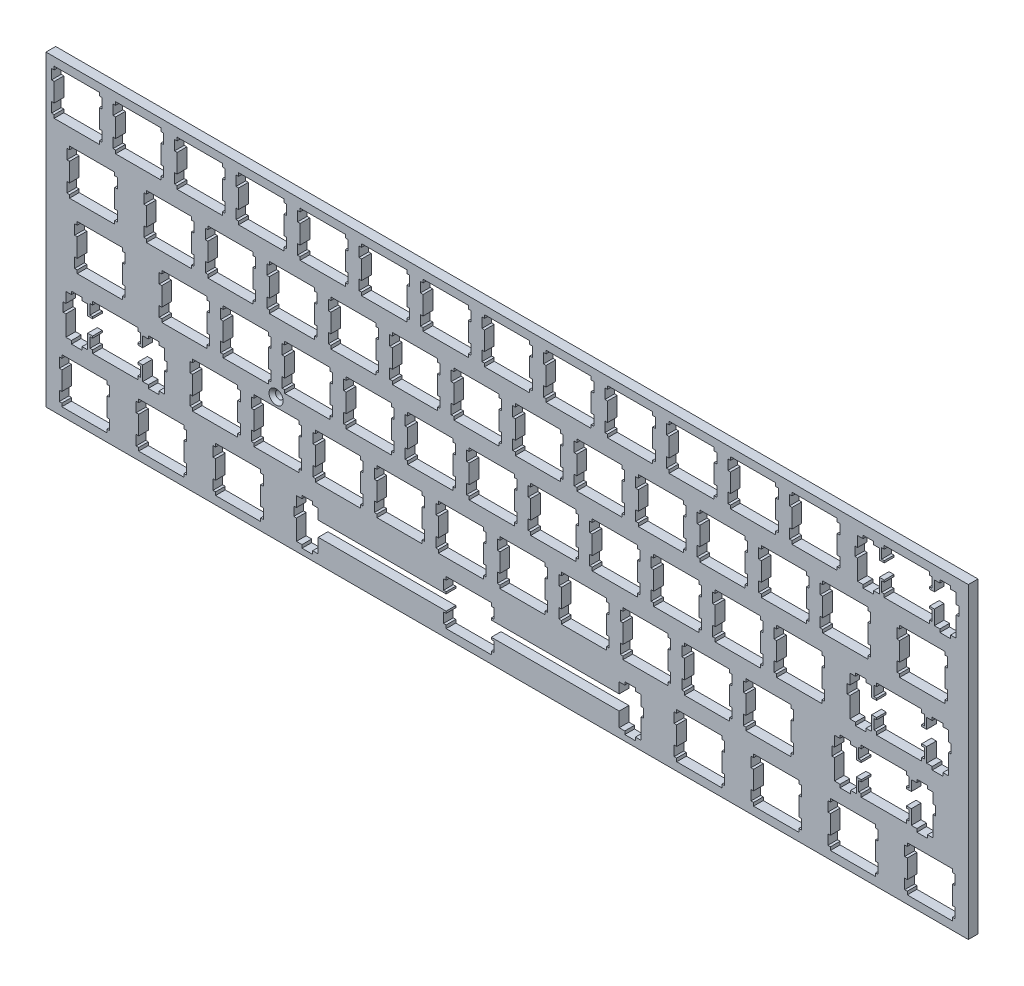
SolidWorks part; units mm, degrees
ref_plane "前视基准面" through (0, 0, 0) normal (0, 0, 1) x (1, 0, 0)
ref_plane "上视基准面" through (0, 0, 0) normal (0, 1, 0) x (1, 0, 0)
ref_plane "右视基准面" through (0, 0, 0) normal (1, 0, 0) x (0, 0, -1)
sketch "Model" plane through (0, 0, 0) normal (0, 0, 1) x (1, 0, 0)
  line L0 (0.0001, 95.2498) -> (285.75, 95.2498)
  line L1 (285.75, 95.2498) -> (285.75, -0.0001)
  line L2 (285.75, -0.0001) -> (0.0001, -0.0001)
  line L3 (0.0001, -0.0001) -> (0.0001, 95.2498)
  line L4 (123.967, 16.5254) -> (123.967, 15.525)
  line L5 (123.967, 15.525) -> (123.168, 15.525)
  line L6 (123.168, 15.525) -> (123.168, 12.4271)
  line L7 (123.168, 12.4271) -> (123.967, 12.4271)
  line L8 (123.967, 12.4271) -> (123.967, 11.8249)
  line L9 (123.967, 11.8249) -> (84.3431, 11.8249)
  line L10 (84.3431, 11.8249) -> (84.3431, 15.0551)
  line L11 (84.3431, 15.0551) -> (82.6176, 15.0551)
  line L12 (82.6176, 15.0551) -> (82.6176, 15.977)
  line L13 (82.6176, 15.977) -> (79.317, 15.977)
  line L14 (79.317, 15.977) -> (79.317, 15.0551)
  line L15 (79.317, 15.0551) -> (77.592, 15.0551)
  line L16 (77.592, 15.0551) -> (77.592, 11.8249)
  line L17 (77.592, 11.8249) -> (76.7679, 11.8249)
  line L18 (76.7679, 11.8249) -> (76.7679, 9.0261)
  line L19 (76.7679, 9.0261) -> (77.592, 9.0261)
  line L20 (77.592, 9.0261) -> (77.592, 2.756)
  line L21 (77.592, 2.756) -> (79.317, 2.756)
  line L22 (79.317, 2.756) -> (79.317, 1.7749)
  line L23 (79.317, 1.7749) -> (82.6176, 1.7749)
  line L24 (82.6176, 1.7749) -> (82.6176, 2.756)
  line L25 (82.6176, 2.756) -> (84.3431, 2.756)
  line L26 (84.3431, 2.756) -> (84.3431, 7.2264)
  line L27 (84.3431, 7.2264) -> (123.967, 7.2264)
  line L28 (123.967, 7.2264) -> (123.967, 6.6255)
  line L29 (123.967, 6.6255) -> (123.168, 6.6255)
  line L30 (123.168, 6.6255) -> (123.168, 3.525)
  line L31 (123.168, 3.525) -> (123.967, 3.525)
  line L32 (123.967, 3.525) -> (123.967, 2.5259)
  line L33 (123.967, 2.5259) -> (137.968, 2.5259)
  line L34 (137.968, 2.5259) -> (137.968, 3.525)
  line L35 (137.968, 3.525) -> (138.767, 3.525)
  line L36 (138.767, 3.525) -> (138.767, 6.6255)
  line L37 (138.767, 6.6255) -> (137.968, 6.6255)
  line L38 (137.968, 6.6255) -> (137.968, 7.2264)
  line L39 (137.968, 7.2264) -> (177.592, 7.2264)
  line L40 (177.592, 7.2264) -> (177.592, 2.756)
  line L41 (177.592, 2.756) -> (179.317, 2.756)
  line L42 (179.317, 2.756) -> (179.317, 1.7749)
  line L43 (179.317, 1.7749) -> (182.618, 1.7749)
  line L44 (182.618, 1.7749) -> (182.618, 2.756)
  line L45 (182.618, 2.756) -> (184.343, 2.756)
  line L46 (184.343, 2.756) -> (184.343, 9.0261)
  line L47 (184.343, 9.0261) -> (185.167, 9.0261)
  line L48 (185.167, 9.0261) -> (185.167, 11.8249)
  line L49 (185.167, 11.8249) -> (184.343, 11.8249)
  line L50 (184.343, 11.8249) -> (184.343, 15.0551)
  line L51 (184.343, 15.0551) -> (182.618, 15.0551)
  line L52 (182.618, 15.0551) -> (182.618, 15.977)
  line L53 (182.618, 15.977) -> (179.317, 15.977)
  line L54 (179.317, 15.977) -> (179.317, 15.0551)
  line L55 (179.317, 15.0551) -> (177.592, 15.0551)
  line L56 (177.592, 15.0551) -> (177.592, 11.8249)
  line L57 (177.592, 11.8249) -> (137.968, 11.8249)
  line L58 (137.968, 11.8249) -> (137.968, 12.4271)
  line L59 (137.968, 12.4271) -> (138.767, 12.4271)
  line L60 (138.767, 12.4271) -> (138.767, 15.525)
  line L61 (138.767, 15.525) -> (137.968, 15.525)
  line L62 (137.968, 15.525) -> (137.968, 16.5254)
  line L63 (137.968, 16.5254) -> (123.967, 16.5254)
  line L64 (266.842, 16.5254) -> (266.842, 15.525)
  line L65 (266.842, 15.525) -> (266.043, 15.525)
  line L66 (266.043, 15.525) -> (266.043, 12.4271)
  line L67 (266.043, 12.4271) -> (266.842, 12.4271)
  line L68 (266.842, 12.4271) -> (266.842, 6.6255)
  line L69 (266.842, 6.6255) -> (266.043, 6.6255)
  line L70 (266.043, 6.6255) -> (266.043, 3.525)
  line L71 (266.043, 3.525) -> (266.842, 3.525)
  line L72 (266.842, 3.525) -> (266.842, 2.5259)
  line L73 (266.842, 2.5259) -> (280.843, 2.5259)
  line L74 (280.843, 2.5259) -> (280.843, 3.525)
  line L75 (280.843, 3.525) -> (281.642, 3.525)
  line L76 (281.642, 3.525) -> (281.642, 6.6255)
  line L77 (281.642, 6.6255) -> (280.843, 6.6255)
  line L78 (280.843, 6.6255) -> (280.843, 12.4271)
  line L79 (280.843, 12.4271) -> (281.642, 12.4271)
  line L80 (281.642, 12.4271) -> (281.642, 15.525)
  line L81 (281.642, 15.525) -> (280.843, 15.525)
  line L82 (280.843, 15.525) -> (280.843, 16.5254)
  line L83 (280.843, 16.5254) -> (266.842, 16.5254)
  line L84 (243.031, 16.5254) -> (243.031, 15.525)
  line L85 (243.031, 15.525) -> (242.23, 15.525)
  line L86 (242.23, 15.525) -> (242.23, 12.4271)
  line L87 (242.23, 12.4271) -> (243.031, 12.4271)
  line L88 (243.031, 12.4271) -> (243.031, 6.6255)
  line L89 (243.031, 6.6255) -> (242.23, 6.6255)
  line L90 (242.23, 6.6255) -> (242.23, 3.525)
  line L91 (242.23, 3.525) -> (243.031, 3.525)
  line L92 (243.031, 3.525) -> (243.031, 2.5259)
  line L93 (243.031, 2.5259) -> (257.03, 2.5259)
  line L94 (257.03, 2.5259) -> (257.03, 3.525)
  line L95 (257.03, 3.525) -> (257.831, 3.525)
  line L96 (257.831, 3.525) -> (257.831, 6.6255)
  line L97 (257.831, 6.6255) -> (257.03, 6.6255)
  line L98 (257.03, 6.6255) -> (257.03, 12.4271)
  line L99 (257.03, 12.4271) -> (257.831, 12.4271)
  line L100 (257.831, 12.4271) -> (257.831, 15.525)
  line L101 (257.831, 15.525) -> (257.03, 15.525)
  line L102 (257.03, 15.525) -> (257.03, 16.5254)
  line L103 (257.03, 16.5254) -> (243.031, 16.5254)
  line L104 (219.217, 16.5254) -> (219.217, 15.525)
  line L105 (219.217, 15.525) -> (218.418, 15.525)
  line L106 (218.418, 15.525) -> (218.418, 12.4271)
  line L107 (218.418, 12.4271) -> (219.217, 12.4271)
  line L108 (219.217, 12.4271) -> (219.217, 6.6255)
  line L109 (219.217, 6.6255) -> (218.418, 6.6255)
  line L110 (218.418, 6.6255) -> (218.418, 3.525)
  line L111 (218.418, 3.525) -> (219.217, 3.525)
  line L112 (219.217, 3.525) -> (219.217, 2.5259)
  line L113 (219.217, 2.5259) -> (233.218, 2.5259)
  line L114 (233.218, 2.5259) -> (233.218, 3.525)
  line L115 (233.218, 3.525) -> (234.017, 3.525)
  line L116 (234.017, 3.525) -> (234.017, 6.6255)
  line L117 (234.017, 6.6255) -> (233.218, 6.6255)
  line L118 (233.218, 6.6255) -> (233.218, 12.4271)
  line L119 (233.218, 12.4271) -> (234.017, 12.4271)
  line L120 (234.017, 12.4271) -> (234.017, 15.525)
  line L121 (234.017, 15.525) -> (233.218, 15.525)
  line L122 (233.218, 15.525) -> (233.218, 16.5254)
  line L123 (233.218, 16.5254) -> (219.217, 16.5254)
  line L124 (195.406, 16.5254) -> (195.406, 15.525)
  line L125 (195.406, 15.525) -> (194.605, 15.525)
  line L126 (194.605, 15.525) -> (194.605, 12.4271)
  line L127 (194.605, 12.4271) -> (195.406, 12.4271)
  line L128 (195.406, 12.4271) -> (195.406, 6.6255)
  line L129 (195.406, 6.6255) -> (194.605, 6.6255)
  line L130 (194.605, 6.6255) -> (194.605, 3.525)
  line L131 (194.605, 3.525) -> (195.406, 3.525)
  line L132 (195.406, 3.525) -> (195.406, 2.5259)
  line L133 (195.406, 2.5259) -> (209.405, 2.5259)
  line L134 (209.405, 2.5259) -> (209.405, 3.525)
  line L135 (209.405, 3.525) -> (210.206, 3.525)
  line L136 (210.206, 3.525) -> (210.206, 6.6255)
  line L137 (210.206, 6.6255) -> (209.405, 6.6255)
  line L138 (209.405, 6.6255) -> (209.405, 12.4271)
  line L139 (209.405, 12.4271) -> (210.206, 12.4271)
  line L140 (210.206, 12.4271) -> (210.206, 15.525)
  line L141 (210.206, 15.525) -> (209.405, 15.525)
  line L142 (209.405, 15.525) -> (209.405, 16.5254)
  line L143 (209.405, 16.5254) -> (195.406, 16.5254)
  line L144 (52.531, 16.5254) -> (52.531, 15.525)
  line L145 (52.531, 15.525) -> (51.7302, 15.525)
  line L146 (51.7302, 15.525) -> (51.7302, 12.4271)
  line L147 (51.7302, 12.4271) -> (52.531, 12.4271)
  line L148 (52.531, 12.4271) -> (52.531, 6.6255)
  line L149 (52.531, 6.6255) -> (51.7302, 6.6255)
  line L150 (51.7302, 6.6255) -> (51.7302, 3.525)
  line L151 (51.7302, 3.525) -> (52.531, 3.525)
  line L152 (52.531, 3.525) -> (52.531, 2.5259)
  line L153 (52.531, 2.5259) -> (66.5303, 2.5259)
  line L154 (66.5303, 2.5259) -> (66.5303, 3.525)
  line L155 (66.5303, 3.525) -> (67.3311, 3.525)
  line L156 (67.3311, 3.525) -> (67.3311, 6.6255)
  line L157 (67.3311, 6.6255) -> (66.5303, 6.6255)
  line L158 (66.5303, 6.6255) -> (66.5303, 12.4271)
  line L159 (66.5303, 12.4271) -> (67.3311, 12.4271)
  line L160 (67.3311, 12.4271) -> (67.3311, 15.525)
  line L161 (67.3311, 15.525) -> (66.5303, 15.525)
  line L162 (66.5303, 15.525) -> (66.5303, 16.5254)
  line L163 (66.5303, 16.5254) -> (52.531, 16.5254)
  line L164 (28.717, 16.5254) -> (28.717, 15.525)
  line L165 (28.717, 15.525) -> (27.9178, 15.525)
  line L166 (27.9178, 15.525) -> (27.9178, 12.4271)
  line L167 (27.9178, 12.4271) -> (28.717, 12.4271)
  line L168 (28.717, 12.4271) -> (28.717, 6.6255)
  line L169 (28.717, 6.6255) -> (27.9178, 6.6255)
  line L170 (27.9178, 6.6255) -> (27.9178, 3.525)
  line L171 (27.9178, 3.525) -> (28.717, 3.525)
  line L172 (28.717, 3.525) -> (28.717, 2.5259)
  line L173 (28.717, 2.5259) -> (42.7178, 2.5259)
  line L174 (42.7178, 2.5259) -> (42.7178, 3.525)
  line L175 (42.7178, 3.525) -> (43.5172, 3.525)
  line L176 (43.5172, 3.525) -> (43.5172, 6.6255)
  line L177 (43.5172, 6.6255) -> (42.7178, 6.6255)
  line L178 (42.7178, 6.6255) -> (42.7178, 12.4271)
  line L179 (42.7178, 12.4271) -> (43.5172, 12.4271)
  line L180 (43.5172, 12.4271) -> (43.5172, 15.525)
  line L181 (43.5172, 15.525) -> (42.7178, 15.525)
  line L182 (42.7178, 15.525) -> (42.7178, 16.5254)
  line L183 (42.7178, 16.5254) -> (28.717, 16.5254)
  line L184 (4.9059, 16.5254) -> (4.9059, 15.525)
  line L185 (4.9059, 15.525) -> (4.1053, 15.525)
  line L186 (4.1053, 15.525) -> (4.1053, 12.4271)
  line L187 (4.1053, 12.4271) -> (4.9059, 12.4271)
  line L188 (4.9059, 12.4271) -> (4.9059, 6.6255)
  line L189 (4.9059, 6.6255) -> (4.1053, 6.6255)
  line L190 (4.1053, 6.6255) -> (4.1053, 3.525)
  line L191 (4.1053, 3.525) -> (4.9059, 3.525)
  line L192 (4.9059, 3.525) -> (4.9059, 2.5259)
  line L193 (4.9059, 2.5259) -> (18.9054, 2.5259)
  line L194 (18.9054, 2.5259) -> (18.9054, 3.525)
  line L195 (18.9054, 3.525) -> (19.706, 3.525)
  line L196 (19.706, 3.525) -> (19.706, 6.6255)
  line L197 (19.706, 6.6255) -> (18.9054, 6.6255)
  line L198 (18.9054, 6.6255) -> (18.9054, 12.4271)
  line L199 (18.9054, 12.4271) -> (19.706, 12.4271)
  line L200 (19.706, 12.4271) -> (19.706, 15.525)
  line L201 (19.706, 15.525) -> (18.9054, 15.525)
  line L202 (18.9054, 15.525) -> (18.9054, 16.5254)
  line L203 (18.9054, 16.5254) -> (4.9059, 16.5254)
  line L204 (252.555, 35.5753) -> (252.555, 34.575)
  line L205 (252.555, 34.575) -> (251.754, 34.575)
  line L206 (251.754, 34.575) -> (251.754, 31.4771)
  line L207 (251.754, 31.4771) -> (252.555, 31.4771)
  line L208 (252.555, 31.4771) -> (252.555, 30.8749)
  line L209 (252.555, 30.8749) -> (251.031, 30.8749)
  line L210 (251.031, 30.8749) -> (251.031, 34.1051)
  line L211 (251.031, 34.1051) -> (249.305, 34.1051)
  line L212 (249.305, 34.1051) -> (249.305, 35.0271)
  line L213 (249.305, 35.0271) -> (246.006, 35.0271)
  line L214 (246.006, 35.0271) -> (246.006, 34.1051)
  line L215 (246.006, 34.1051) -> (244.281, 34.1051)
  line L216 (244.281, 34.1051) -> (244.281, 30.8749)
  line L217 (244.281, 30.8749) -> (243.455, 30.8749)
  line L218 (243.455, 30.8749) -> (243.455, 28.0761)
  line L219 (243.455, 28.0761) -> (244.281, 28.0761)
  line L220 (244.281, 28.0761) -> (244.281, 21.8061)
  line L221 (244.281, 21.8061) -> (246.006, 21.8061)
  line L222 (246.006, 21.8061) -> (246.006, 20.8249)
  line L223 (246.006, 20.8249) -> (249.305, 20.8249)
  line L224 (249.305, 20.8249) -> (249.305, 21.8061)
  line L225 (249.305, 21.8061) -> (251.031, 21.8061)
  line L226 (251.031, 21.8061) -> (251.031, 26.275)
  line L227 (251.031, 26.275) -> (252.555, 26.275)
  line L228 (252.555, 26.275) -> (252.555, 25.6756)
  line L229 (252.555, 25.6756) -> (251.754, 25.6756)
  line L230 (251.754, 25.6756) -> (251.754, 22.575)
  line L231 (251.754, 22.575) -> (252.555, 22.575)
  line L232 (252.555, 22.575) -> (252.555, 21.5759)
  line L233 (252.555, 21.5759) -> (266.555, 21.5759)
  line L234 (266.555, 21.5759) -> (266.555, 22.575)
  line L235 (266.555, 22.575) -> (267.356, 22.575)
  line L236 (267.356, 22.575) -> (267.356, 25.6756)
  line L237 (267.356, 25.6756) -> (266.555, 25.6756)
  line L238 (266.555, 25.6756) -> (266.555, 26.275)
  line L239 (266.555, 26.275) -> (268.081, 26.275)
  line L240 (268.081, 26.275) -> (268.081, 21.8061)
  line L241 (268.081, 21.8061) -> (269.805, 21.8061)
  line L242 (269.805, 21.8061) -> (269.805, 20.8249)
  line L243 (269.805, 20.8249) -> (273.105, 20.8249)
  line L244 (273.105, 20.8249) -> (273.105, 21.8061)
  line L245 (273.105, 21.8061) -> (274.83, 21.8061)
  line L246 (274.83, 21.8061) -> (274.83, 28.0761)
  line L247 (274.83, 28.0761) -> (275.656, 28.0761)
  line L248 (275.656, 28.0761) -> (275.656, 30.8749)
  line L249 (275.656, 30.8749) -> (274.83, 30.8749)
  line L250 (274.83, 30.8749) -> (274.83, 34.1051)
  line L251 (274.83, 34.1051) -> (273.105, 34.1051)
  line L252 (273.105, 34.1051) -> (273.105, 35.0271)
  line L253 (273.105, 35.0271) -> (269.805, 35.0271)
  line L254 (269.805, 35.0271) -> (269.805, 34.1051)
  line L255 (269.805, 34.1051) -> (268.081, 34.1051)
  line L256 (268.081, 34.1051) -> (268.081, 30.8749)
  line L257 (268.081, 30.8749) -> (266.555, 30.8749)
  line L258 (266.555, 30.8749) -> (266.555, 31.4771)
  line L259 (266.555, 31.4771) -> (267.356, 31.4771)
  line L260 (267.356, 31.4771) -> (267.356, 34.575)
  line L261 (267.356, 34.575) -> (266.555, 34.575)
  line L262 (266.555, 34.575) -> (266.555, 35.5753)
  line L263 (266.555, 35.5753) -> (252.555, 35.5753)
  line L264 (14.4309, 35.5753) -> (14.4309, 34.575)
  line L265 (14.4309, 34.575) -> (13.6303, 34.575)
  line L266 (13.6303, 34.575) -> (13.6303, 31.4771)
  line L267 (13.6303, 31.4771) -> (14.4309, 31.4771)
  line L268 (14.4309, 31.4771) -> (14.4309, 30.8749)
  line L269 (14.4309, 30.8749) -> (12.9054, 30.8749)
  line L270 (12.9054, 30.8749) -> (12.9054, 34.1051)
  line L271 (12.9054, 34.1051) -> (11.1801, 34.1051)
  line L272 (11.1801, 34.1051) -> (11.1801, 35.0271)
  line L273 (11.1801, 35.0271) -> (7.8811, 35.0271)
  line L274 (7.8811, 35.0271) -> (7.8811, 34.1051)
  line L275 (7.8811, 34.1051) -> (6.1558, 34.1051)
  line L276 (6.1558, 34.1051) -> (6.1558, 30.8749)
  line L277 (6.1558, 30.8749) -> (5.3303, 30.8749)
  line L278 (5.3303, 30.8749) -> (5.3303, 28.0761)
  line L279 (5.3303, 28.0761) -> (6.1558, 28.0761)
  line L280 (6.1558, 28.0761) -> (6.1558, 21.8061)
  line L281 (6.1558, 21.8061) -> (7.8811, 21.8061)
  line L282 (7.8811, 21.8061) -> (7.8811, 20.8249)
  line L283 (7.8811, 20.8249) -> (11.1801, 20.8249)
  line L284 (11.1801, 20.8249) -> (11.1801, 21.8061)
  line L285 (11.1801, 21.8061) -> (12.9054, 21.8061)
  line L286 (12.9054, 21.8061) -> (12.9054, 26.275)
  line L287 (12.9054, 26.275) -> (14.4309, 26.275)
  line L288 (14.4309, 26.275) -> (14.4309, 25.6756)
  line L289 (14.4309, 25.6756) -> (13.6303, 25.6756)
  line L290 (13.6303, 25.6756) -> (13.6303, 22.575)
  line L291 (13.6303, 22.575) -> (14.4309, 22.575)
  line L292 (14.4309, 22.575) -> (14.4309, 21.5759)
  line L293 (14.4309, 21.5759) -> (28.4304, 21.5759)
  line L294 (28.4304, 21.5759) -> (28.4304, 22.575)
  line L295 (28.4304, 22.575) -> (29.231, 22.575)
  line L296 (29.231, 22.575) -> (29.231, 25.6756)
  line L297 (29.231, 25.6756) -> (28.4304, 25.6756)
  line L298 (28.4304, 25.6756) -> (28.4304, 26.275)
  line L299 (28.4304, 26.275) -> (29.9559, 26.275)
  line L300 (29.9559, 26.275) -> (29.9559, 21.8061)
  line L301 (29.9559, 21.8061) -> (31.6798, 21.8061)
  line L302 (31.6798, 21.8061) -> (31.6798, 20.8249)
  line L303 (31.6798, 20.8249) -> (34.9802, 20.8249)
  line L304 (34.9802, 20.8249) -> (34.9802, 21.8061)
  line L305 (34.9802, 21.8061) -> (36.7054, 21.8061)
  line L306 (36.7054, 21.8061) -> (36.7054, 28.0761)
  line L307 (36.7054, 28.0761) -> (37.5309, 28.0761)
  line L308 (37.5309, 28.0761) -> (37.5309, 30.8749)
  line L309 (37.5309, 30.8749) -> (36.7054, 30.8749)
  line L310 (36.7054, 30.8749) -> (36.7054, 34.1051)
  line L311 (36.7054, 34.1051) -> (34.9802, 34.1051)
  line L312 (34.9802, 34.1051) -> (34.9802, 35.0271)
  line L313 (34.9802, 35.0271) -> (31.6798, 35.0271)
  line L314 (31.6798, 35.0271) -> (31.6798, 34.1051)
  line L315 (31.6798, 34.1051) -> (29.9559, 34.1051)
  line L316 (29.9559, 34.1051) -> (29.9559, 30.8749)
  line L317 (29.9559, 30.8749) -> (28.4304, 30.8749)
  line L318 (28.4304, 30.8749) -> (28.4304, 31.4771)
  line L319 (28.4304, 31.4771) -> (29.231, 31.4771)
  line L320 (29.231, 31.4771) -> (29.231, 34.575)
  line L321 (29.231, 34.575) -> (28.4304, 34.575)
  line L322 (28.4304, 34.575) -> (28.4304, 35.5753)
  line L323 (28.4304, 35.5753) -> (14.4309, 35.5753)
  line L324 (216.837, 35.5753) -> (216.837, 34.575)
  line L325 (216.837, 34.575) -> (216.036, 34.575)
  line L326 (216.036, 34.575) -> (216.036, 31.4771)
  line L327 (216.036, 31.4771) -> (216.837, 31.4771)
  line L328 (216.837, 31.4771) -> (216.837, 25.6756)
  line L329 (216.837, 25.6756) -> (216.036, 25.6756)
  line L330 (216.036, 25.6756) -> (216.036, 22.575)
  line L331 (216.036, 22.575) -> (216.837, 22.575)
  line L332 (216.837, 22.575) -> (216.837, 21.5759)
  line L333 (216.837, 21.5759) -> (230.837, 21.5759)
  line L334 (230.837, 21.5759) -> (230.837, 22.575)
  line L335 (230.837, 22.575) -> (231.636, 22.575)
  line L336 (231.636, 22.575) -> (231.636, 25.6756)
  line L337 (231.636, 25.6756) -> (230.837, 25.6756)
  line L338 (230.837, 25.6756) -> (230.837, 31.4771)
  line L339 (230.837, 31.4771) -> (231.636, 31.4771)
  line L340 (231.636, 31.4771) -> (231.636, 34.575)
  line L341 (231.636, 34.575) -> (230.837, 34.575)
  line L342 (230.837, 34.575) -> (230.837, 35.5753)
  line L343 (230.837, 35.5753) -> (216.837, 35.5753)
  line L344 (197.787, 35.5753) -> (197.787, 34.575)
  line L345 (197.787, 34.575) -> (196.986, 34.575)
  line L346 (196.986, 34.575) -> (196.986, 31.4771)
  line L347 (196.986, 31.4771) -> (197.787, 31.4771)
  line L348 (197.787, 31.4771) -> (197.787, 25.6756)
  line L349 (197.787, 25.6756) -> (196.986, 25.6756)
  line L350 (196.986, 25.6756) -> (196.986, 22.575)
  line L351 (196.986, 22.575) -> (197.787, 22.575)
  line L352 (197.787, 22.575) -> (197.787, 21.5759)
  line L353 (197.787, 21.5759) -> (211.787, 21.5759)
  line L354 (211.787, 21.5759) -> (211.787, 22.575)
  line L355 (211.787, 22.575) -> (212.586, 22.575)
  line L356 (212.586, 22.575) -> (212.586, 25.6756)
  line L357 (212.586, 25.6756) -> (211.787, 25.6756)
  line L358 (211.787, 25.6756) -> (211.787, 31.4771)
  line L359 (211.787, 31.4771) -> (212.586, 31.4771)
  line L360 (212.586, 31.4771) -> (212.586, 34.575)
  line L361 (212.586, 34.575) -> (211.787, 34.575)
  line L362 (211.787, 34.575) -> (211.787, 35.5753)
  line L363 (211.787, 35.5753) -> (197.787, 35.5753)
  line L364 (178.737, 35.5753) -> (178.737, 34.575)
  line L365 (178.737, 34.575) -> (177.936, 34.575)
  line L366 (177.936, 34.575) -> (177.936, 31.4771)
  line L367 (177.936, 31.4771) -> (178.737, 31.4771)
  line L368 (178.737, 31.4771) -> (178.737, 25.6756)
  line L369 (178.737, 25.6756) -> (177.936, 25.6756)
  line L370 (177.936, 25.6756) -> (177.936, 22.575)
  line L371 (177.936, 22.575) -> (178.737, 22.575)
  line L372 (178.737, 22.575) -> (178.737, 21.5759)
  line L373 (178.737, 21.5759) -> (192.737, 21.5759)
  line L374 (192.737, 21.5759) -> (192.737, 22.575)
  line L375 (192.737, 22.575) -> (193.536, 22.575)
  line L376 (193.536, 22.575) -> (193.536, 25.6756)
  line L377 (193.536, 25.6756) -> (192.737, 25.6756)
  line L378 (192.737, 25.6756) -> (192.737, 31.4771)
  line L379 (192.737, 31.4771) -> (193.536, 31.4771)
  line L380 (193.536, 31.4771) -> (193.536, 34.575)
  line L381 (193.536, 34.575) -> (192.737, 34.575)
  line L382 (192.737, 34.575) -> (192.737, 35.5753)
  line L383 (192.737, 35.5753) -> (178.737, 35.5753)
  line L384 (159.687, 35.5753) -> (159.687, 34.575)
  line L385 (159.687, 34.575) -> (158.886, 34.575)
  line L386 (158.886, 34.575) -> (158.886, 31.4771)
  line L387 (158.886, 31.4771) -> (159.687, 31.4771)
  line L388 (159.687, 31.4771) -> (159.687, 25.6756)
  line L389 (159.687, 25.6756) -> (158.886, 25.6756)
  line L390 (158.886, 25.6756) -> (158.886, 22.575)
  line L391 (158.886, 22.575) -> (159.687, 22.575)
  line L392 (159.687, 22.575) -> (159.687, 21.5759)
  line L393 (159.687, 21.5759) -> (173.687, 21.5759)
  line L394 (173.687, 21.5759) -> (173.687, 22.575)
  line L395 (173.687, 22.575) -> (174.486, 22.575)
  line L396 (174.486, 22.575) -> (174.486, 25.6756)
  line L397 (174.486, 25.6756) -> (173.687, 25.6756)
  line L398 (173.687, 25.6756) -> (173.687, 31.4771)
  line L399 (173.687, 31.4771) -> (174.486, 31.4771)
  line L400 (174.486, 31.4771) -> (174.486, 34.575)
  line L401 (174.486, 34.575) -> (173.687, 34.575)
  line L402 (173.687, 34.575) -> (173.687, 35.5753)
  line L403 (173.687, 35.5753) -> (159.687, 35.5753)
  line L404 (140.637, 35.5753) -> (140.637, 34.575)
  line L405 (140.637, 34.575) -> (139.836, 34.575)
  line L406 (139.836, 34.575) -> (139.836, 31.4771)
  line L407 (139.836, 31.4771) -> (140.637, 31.4771)
  line L408 (140.637, 31.4771) -> (140.637, 25.6756)
  line L409 (140.637, 25.6756) -> (139.836, 25.6756)
  line L410 (139.836, 25.6756) -> (139.836, 22.575)
  line L411 (139.836, 22.575) -> (140.637, 22.575)
  line L412 (140.637, 22.575) -> (140.637, 21.5759)
  line L413 (140.637, 21.5759) -> (154.637, 21.5759)
  line L414 (154.637, 21.5759) -> (154.637, 22.575)
  line L415 (154.637, 22.575) -> (155.436, 22.575)
  line L416 (155.436, 22.575) -> (155.436, 25.6756)
  line L417 (155.436, 25.6756) -> (154.637, 25.6756)
  line L418 (154.637, 25.6756) -> (154.637, 31.4771)
  line L419 (154.637, 31.4771) -> (155.436, 31.4771)
  line L420 (155.436, 31.4771) -> (155.436, 34.575)
  line L421 (155.436, 34.575) -> (154.637, 34.575)
  line L422 (154.637, 34.575) -> (154.637, 35.5753)
  line L423 (154.637, 35.5753) -> (140.637, 35.5753)
  line L424 (121.587, 35.5753) -> (121.587, 34.575)
  line L425 (121.587, 34.575) -> (120.786, 34.575)
  line L426 (120.786, 34.575) -> (120.786, 31.4771)
  line L427 (120.786, 31.4771) -> (121.587, 31.4771)
  line L428 (121.587, 31.4771) -> (121.587, 25.6756)
  line L429 (121.587, 25.6756) -> (120.786, 25.6756)
  line L430 (120.786, 25.6756) -> (120.786, 22.575)
  line L431 (120.786, 22.575) -> (121.587, 22.575)
  line L432 (121.587, 22.575) -> (121.587, 21.5759)
  line L433 (121.587, 21.5759) -> (135.587, 21.5759)
  line L434 (135.587, 21.5759) -> (135.587, 22.575)
  line L435 (135.587, 22.575) -> (136.386, 22.575)
  line L436 (136.386, 22.575) -> (136.386, 25.6756)
  line L437 (136.386, 25.6756) -> (135.587, 25.6756)
  line L438 (135.587, 25.6756) -> (135.587, 31.4771)
  line L439 (135.587, 31.4771) -> (136.386, 31.4771)
  line L440 (136.386, 31.4771) -> (136.386, 34.575)
  line L441 (136.386, 34.575) -> (135.587, 34.575)
  line L442 (135.587, 34.575) -> (135.587, 35.5753)
  line L443 (135.587, 35.5753) -> (121.587, 35.5753)
  line L444 (102.537, 35.5753) -> (102.537, 34.575)
  line L445 (102.537, 34.575) -> (101.736, 34.575)
  line L446 (101.736, 34.575) -> (101.736, 31.4771)
  line L447 (101.736, 31.4771) -> (102.537, 31.4771)
  line L448 (102.537, 31.4771) -> (102.537, 25.6756)
  line L449 (102.537, 25.6756) -> (101.736, 25.6756)
  line L450 (101.736, 25.6756) -> (101.736, 22.575)
  line L451 (101.736, 22.575) -> (102.537, 22.575)
  line L452 (102.537, 22.575) -> (102.537, 21.5759)
  line L453 (102.537, 21.5759) -> (116.537, 21.5759)
  line L454 (116.537, 21.5759) -> (116.537, 22.575)
  line L455 (116.537, 22.575) -> (117.336, 22.575)
  line L456 (117.336, 22.575) -> (117.336, 25.6756)
  line L457 (117.336, 25.6756) -> (116.537, 25.6756)
  line L458 (116.537, 25.6756) -> (116.537, 31.4771)
  line L459 (116.537, 31.4771) -> (117.336, 31.4771)
  line L460 (117.336, 31.4771) -> (117.336, 34.575)
  line L461 (117.336, 34.575) -> (116.537, 34.575)
  line L462 (116.537, 34.575) -> (116.537, 35.5753)
  line L463 (116.537, 35.5753) -> (102.537, 35.5753)
  line L464 (83.4872, 35.5753) -> (83.4872, 34.575)
  line L465 (83.4872, 34.575) -> (82.6864, 34.575)
  line L466 (82.6864, 34.575) -> (82.6864, 31.4771)
  line L467 (82.6864, 31.4771) -> (83.4872, 31.4771)
  line L468 (83.4872, 31.4771) -> (83.4872, 25.6756)
  line L469 (83.4872, 25.6756) -> (82.6864, 25.6756)
  line L470 (82.6864, 25.6756) -> (82.6864, 22.575)
  line L471 (82.6864, 22.575) -> (83.4872, 22.575)
  line L472 (83.4872, 22.575) -> (83.4872, 21.5759)
  line L473 (83.4872, 21.5759) -> (97.4865, 21.5759)
  line L474 (97.4865, 21.5759) -> (97.4865, 22.575)
  line L475 (97.4865, 22.575) -> (98.2859, 22.575)
  line L476 (98.2859, 22.575) -> (98.2859, 25.6756)
  line L477 (98.2859, 25.6756) -> (97.4865, 25.6756)
  line L478 (97.4865, 25.6756) -> (97.4865, 31.4771)
  line L479 (97.4865, 31.4771) -> (98.2859, 31.4771)
  line L480 (98.2859, 31.4771) -> (98.2859, 34.575)
  line L481 (98.2859, 34.575) -> (97.4865, 34.575)
  line L482 (97.4865, 34.575) -> (97.4865, 35.5753)
  line L483 (97.4865, 35.5753) -> (83.4872, 35.5753)
  line L484 (64.4372, 35.5753) -> (64.4372, 34.575)
  line L485 (64.4372, 34.575) -> (63.6364, 34.575)
  line L486 (63.6364, 34.575) -> (63.6364, 31.4771)
  line L487 (63.6364, 31.4771) -> (64.4372, 31.4771)
  line L488 (64.4372, 31.4771) -> (64.4372, 25.6756)
  line L489 (64.4372, 25.6756) -> (63.6364, 25.6756)
  line L490 (63.6364, 25.6756) -> (63.6364, 22.575)
  line L491 (63.6364, 22.575) -> (64.4372, 22.575)
  line L492 (64.4372, 22.575) -> (64.4372, 21.5759)
  line L493 (64.4372, 21.5759) -> (78.4365, 21.5759)
  line L494 (78.4365, 21.5759) -> (78.4365, 22.575)
  line L495 (78.4365, 22.575) -> (79.2359, 22.575)
  line L496 (79.2359, 22.575) -> (79.2359, 25.6756)
  line L497 (79.2359, 25.6756) -> (78.4365, 25.6756)
  line L498 (78.4365, 25.6756) -> (78.4365, 31.4771)
  line L499 (78.4365, 31.4771) -> (79.2359, 31.4771)
  line L500 (79.2359, 31.4771) -> (79.2359, 34.575)
  line L501 (79.2359, 34.575) -> (78.4365, 34.575)
  line L502 (78.4365, 34.575) -> (78.4365, 35.5753)
  line L503 (78.4365, 35.5753) -> (64.4372, 35.5753)
  line L504 (45.3872, 35.5753) -> (45.3872, 34.575)
  line L505 (45.3872, 34.575) -> (44.5864, 34.575)
  line L506 (44.5864, 34.575) -> (44.5864, 31.4771)
  line L507 (44.5864, 31.4771) -> (45.3872, 31.4771)
  line L508 (45.3872, 31.4771) -> (45.3872, 25.6756)
  line L509 (45.3872, 25.6756) -> (44.5864, 25.6756)
  line L510 (44.5864, 25.6756) -> (44.5864, 22.575)
  line L511 (44.5864, 22.575) -> (45.3872, 22.575)
  line L512 (45.3872, 22.575) -> (45.3872, 21.5759)
  line L513 (45.3872, 21.5759) -> (59.3865, 21.5759)
  line L514 (59.3865, 21.5759) -> (59.3865, 22.575)
  line L515 (59.3865, 22.575) -> (60.1859, 22.575)
  line L516 (60.1859, 22.575) -> (60.1859, 25.6756)
  line L517 (60.1859, 25.6756) -> (59.3865, 25.6756)
  line L518 (59.3865, 25.6756) -> (59.3865, 31.4771)
  line L519 (59.3865, 31.4771) -> (60.1859, 31.4771)
  line L520 (60.1859, 31.4771) -> (60.1859, 34.575)
  line L521 (60.1859, 34.575) -> (59.3865, 34.575)
  line L522 (59.3865, 34.575) -> (59.3865, 35.5753)
  line L523 (59.3865, 35.5753) -> (45.3872, 35.5753)
  line L524 (257.317, 54.6254) -> (257.317, 53.6249)
  line L525 (257.317, 53.6249) -> (256.516, 53.6249)
  line L526 (256.516, 53.6249) -> (256.516, 50.5257)
  line L527 (256.516, 50.5257) -> (257.317, 50.5257)
  line L528 (257.317, 50.5257) -> (257.317, 49.9249)
  line L529 (257.317, 49.9249) -> (255.793, 49.9249)
  line L530 (255.793, 49.9249) -> (255.793, 53.155)
  line L531 (255.793, 53.155) -> (254.066, 53.155)
  line L532 (254.066, 53.155) -> (254.066, 54.0757)
  line L533 (254.066, 54.0757) -> (250.767, 54.0757)
  line L534 (250.767, 54.0757) -> (250.767, 53.155)
  line L535 (250.767, 53.155) -> (249.042, 53.155)
  line L536 (249.042, 53.155) -> (249.042, 49.9249)
  line L537 (249.042, 49.9249) -> (248.218, 49.9249)
  line L538 (248.218, 49.9249) -> (248.218, 47.126)
  line L539 (248.218, 47.126) -> (249.042, 47.126)
  line L540 (249.042, 47.126) -> (249.042, 40.8561)
  line L541 (249.042, 40.8561) -> (250.767, 40.8561)
  line L542 (250.767, 40.8561) -> (250.767, 39.875)
  line L543 (250.767, 39.875) -> (254.066, 39.875)
  line L544 (254.066, 39.875) -> (254.066, 40.8561)
  line L545 (254.066, 40.8561) -> (255.793, 40.8561)
  line L546 (255.793, 40.8561) -> (255.793, 45.3251)
  line L547 (255.793, 45.3251) -> (257.317, 45.3251)
  line L548 (257.317, 45.3251) -> (257.317, 44.7257)
  line L549 (257.317, 44.7257) -> (256.516, 44.7257)
  line L550 (256.516, 44.7257) -> (256.516, 41.6251)
  line L551 (256.516, 41.6251) -> (257.317, 41.6251)
  line L552 (257.317, 41.6251) -> (257.317, 40.6261)
  line L553 (257.317, 40.6261) -> (271.318, 40.6261)
  line L554 (271.318, 40.6261) -> (271.318, 41.6251)
  line L555 (271.318, 41.6251) -> (272.117, 41.6251)
  line L556 (272.117, 41.6251) -> (272.117, 44.7257)
  line L557 (272.117, 44.7257) -> (271.318, 44.7257)
  line L558 (271.318, 44.7257) -> (271.318, 45.3251)
  line L559 (271.318, 45.3251) -> (272.842, 45.3251)
  line L560 (272.842, 45.3251) -> (272.842, 40.8561)
  line L561 (272.842, 40.8561) -> (274.567, 40.8561)
  line L562 (274.567, 40.8561) -> (274.567, 39.875)
  line L563 (274.567, 39.875) -> (277.868, 39.875)
  line L564 (277.868, 39.875) -> (277.868, 40.8561)
  line L565 (277.868, 40.8561) -> (279.593, 40.8561)
  line L566 (279.593, 40.8561) -> (279.593, 47.126)
  line L567 (279.593, 47.126) -> (280.417, 47.126)
  line L568 (280.417, 47.126) -> (280.417, 49.9249)
  line L569 (280.417, 49.9249) -> (279.593, 49.9249)
  line L570 (279.593, 49.9249) -> (279.593, 53.155)
  line L571 (279.593, 53.155) -> (277.868, 53.155)
  line L572 (277.868, 53.155) -> (277.868, 54.0757)
  line L573 (277.868, 54.0757) -> (274.567, 54.0757)
  line L574 (274.567, 54.0757) -> (274.567, 53.155)
  line L575 (274.567, 53.155) -> (272.842, 53.155)
  line L576 (272.842, 53.155) -> (272.842, 49.9249)
  line L577 (272.842, 49.9249) -> (271.318, 49.9249)
  line L578 (271.318, 49.9249) -> (271.318, 50.5257)
  line L579 (271.318, 50.5257) -> (272.117, 50.5257)
  line L580 (272.117, 50.5257) -> (272.117, 53.6249)
  line L581 (272.117, 53.6249) -> (271.318, 53.6249)
  line L582 (271.318, 53.6249) -> (271.318, 54.6254)
  line L583 (271.318, 54.6254) -> (257.317, 54.6254)
  line L584 (226.362, 54.6254) -> (226.362, 53.6249)
  line L585 (226.362, 53.6249) -> (225.561, 53.6249)
  line L586 (225.561, 53.6249) -> (225.561, 50.5257)
  line L587 (225.561, 50.5257) -> (226.362, 50.5257)
  line L588 (226.362, 50.5257) -> (226.362, 44.7257)
  line L589 (226.362, 44.7257) -> (225.561, 44.7257)
  line L590 (225.561, 44.7257) -> (225.561, 41.6251)
  line L591 (225.561, 41.6251) -> (226.362, 41.6251)
  line L592 (226.362, 41.6251) -> (226.362, 40.6261)
  line L593 (226.362, 40.6261) -> (240.362, 40.6261)
  line L594 (240.362, 40.6261) -> (240.362, 41.6251)
  line L595 (240.362, 41.6251) -> (241.161, 41.6251)
  line L596 (241.161, 41.6251) -> (241.161, 44.7257)
  line L597 (241.161, 44.7257) -> (240.362, 44.7257)
  line L598 (240.362, 44.7257) -> (240.362, 50.5257)
  line L599 (240.362, 50.5257) -> (241.161, 50.5257)
  line L600 (241.161, 50.5257) -> (241.161, 53.6249)
  line L601 (241.161, 53.6249) -> (240.362, 53.6249)
  line L602 (240.362, 53.6249) -> (240.362, 54.6254)
  line L603 (240.362, 54.6254) -> (226.362, 54.6254)
  line L604 (207.312, 54.6254) -> (207.312, 53.6249)
  line L605 (207.312, 53.6249) -> (206.511, 53.6249)
  line L606 (206.511, 53.6249) -> (206.511, 50.5257)
  line L607 (206.511, 50.5257) -> (207.312, 50.5257)
  line L608 (207.312, 50.5257) -> (207.312, 44.7257)
  line L609 (207.312, 44.7257) -> (206.511, 44.7257)
  line L610 (206.511, 44.7257) -> (206.511, 41.6251)
  line L611 (206.511, 41.6251) -> (207.312, 41.6251)
  line L612 (207.312, 41.6251) -> (207.312, 40.6261)
  line L613 (207.312, 40.6261) -> (221.312, 40.6261)
  line L614 (221.312, 40.6261) -> (221.312, 41.6251)
  line L615 (221.312, 41.6251) -> (222.111, 41.6251)
  line L616 (222.111, 41.6251) -> (222.111, 44.7257)
  line L617 (222.111, 44.7257) -> (221.312, 44.7257)
  line L618 (221.312, 44.7257) -> (221.312, 50.5257)
  line L619 (221.312, 50.5257) -> (222.111, 50.5257)
  line L620 (222.111, 50.5257) -> (222.111, 53.6249)
  line L621 (222.111, 53.6249) -> (221.312, 53.6249)
  line L622 (221.312, 53.6249) -> (221.312, 54.6254)
  line L623 (221.312, 54.6254) -> (207.312, 54.6254)
  line L624 (188.262, 54.6254) -> (188.262, 53.6249)
  line L625 (188.262, 53.6249) -> (187.461, 53.6249)
  line L626 (187.461, 53.6249) -> (187.461, 50.5257)
  line L627 (187.461, 50.5257) -> (188.262, 50.5257)
  line L628 (188.262, 50.5257) -> (188.262, 44.7257)
  line L629 (188.262, 44.7257) -> (187.461, 44.7257)
  line L630 (187.461, 44.7257) -> (187.461, 41.6251)
  line L631 (187.461, 41.6251) -> (188.262, 41.6251)
  line L632 (188.262, 41.6251) -> (188.262, 40.6261)
  line L633 (188.262, 40.6261) -> (202.262, 40.6261)
  line L634 (202.262, 40.6261) -> (202.262, 41.6251)
  line L635 (202.262, 41.6251) -> (203.061, 41.6251)
  line L636 (203.061, 41.6251) -> (203.061, 44.7257)
  line L637 (203.061, 44.7257) -> (202.262, 44.7257)
  line L638 (202.262, 44.7257) -> (202.262, 50.5257)
  line L639 (202.262, 50.5257) -> (203.061, 50.5257)
  line L640 (203.061, 50.5257) -> (203.061, 53.6249)
  line L641 (203.061, 53.6249) -> (202.262, 53.6249)
  line L642 (202.262, 53.6249) -> (202.262, 54.6254)
  line L643 (202.262, 54.6254) -> (188.262, 54.6254)
  line L644 (169.212, 54.6254) -> (169.212, 53.6249)
  line L645 (169.212, 53.6249) -> (168.411, 53.6249)
  line L646 (168.411, 53.6249) -> (168.411, 50.5257)
  line L647 (168.411, 50.5257) -> (169.212, 50.5257)
  line L648 (169.212, 50.5257) -> (169.212, 44.7257)
  line L649 (169.212, 44.7257) -> (168.411, 44.7257)
  line L650 (168.411, 44.7257) -> (168.411, 41.6251)
  line L651 (168.411, 41.6251) -> (169.212, 41.6251)
  line L652 (169.212, 41.6251) -> (169.212, 40.6261)
  line L653 (169.212, 40.6261) -> (183.212, 40.6261)
  line L654 (183.212, 40.6261) -> (183.212, 41.6251)
  line L655 (183.212, 41.6251) -> (184.011, 41.6251)
  line L656 (184.011, 41.6251) -> (184.011, 44.7257)
  line L657 (184.011, 44.7257) -> (183.212, 44.7257)
  line L658 (183.212, 44.7257) -> (183.212, 50.5257)
  line L659 (183.212, 50.5257) -> (184.011, 50.5257)
  line L660 (184.011, 50.5257) -> (184.011, 53.6249)
  line L661 (184.011, 53.6249) -> (183.212, 53.6249)
  line L662 (183.212, 53.6249) -> (183.212, 54.6254)
  line L663 (183.212, 54.6254) -> (169.212, 54.6254)
  line L664 (150.162, 54.6254) -> (150.162, 53.6249)
  line L665 (150.162, 53.6249) -> (149.361, 53.6249)
  line L666 (149.361, 53.6249) -> (149.361, 50.5257)
  line L667 (149.361, 50.5257) -> (150.162, 50.5257)
  line L668 (150.162, 50.5257) -> (150.162, 44.7257)
  line L669 (150.162, 44.7257) -> (149.361, 44.7257)
  line L670 (149.361, 44.7257) -> (149.361, 41.6251)
  line L671 (149.361, 41.6251) -> (150.162, 41.6251)
  line L672 (150.162, 41.6251) -> (150.162, 40.6261)
  line L673 (150.162, 40.6261) -> (164.162, 40.6261)
  line L674 (164.162, 40.6261) -> (164.162, 41.6251)
  line L675 (164.162, 41.6251) -> (164.961, 41.6251)
  line L676 (164.961, 41.6251) -> (164.961, 44.7257)
  line L677 (164.961, 44.7257) -> (164.162, 44.7257)
  line L678 (164.162, 44.7257) -> (164.162, 50.5257)
  line L679 (164.162, 50.5257) -> (164.961, 50.5257)
  line L680 (164.961, 50.5257) -> (164.961, 53.6249)
  line L681 (164.961, 53.6249) -> (164.162, 53.6249)
  line L682 (164.162, 53.6249) -> (164.162, 54.6254)
  line L683 (164.162, 54.6254) -> (150.162, 54.6254)
  line L684 (131.112, 54.6254) -> (131.112, 53.6249)
  line L685 (131.112, 53.6249) -> (130.311, 53.6249)
  line L686 (130.311, 53.6249) -> (130.311, 50.5257)
  line L687 (130.311, 50.5257) -> (131.112, 50.5257)
  line L688 (131.112, 50.5257) -> (131.112, 44.7257)
  line L689 (131.112, 44.7257) -> (130.311, 44.7257)
  line L690 (130.311, 44.7257) -> (130.311, 41.6251)
  line L691 (130.311, 41.6251) -> (131.112, 41.6251)
  line L692 (131.112, 41.6251) -> (131.112, 40.6261)
  line L693 (131.112, 40.6261) -> (145.112, 40.6261)
  line L694 (145.112, 40.6261) -> (145.112, 41.6251)
  line L695 (145.112, 41.6251) -> (145.911, 41.6251)
  line L696 (145.911, 41.6251) -> (145.911, 44.7257)
  line L697 (145.911, 44.7257) -> (145.112, 44.7257)
  line L698 (145.112, 44.7257) -> (145.112, 50.5257)
  line L699 (145.112, 50.5257) -> (145.911, 50.5257)
  line L700 (145.911, 50.5257) -> (145.911, 53.6249)
  line L701 (145.911, 53.6249) -> (145.112, 53.6249)
  line L702 (145.112, 53.6249) -> (145.112, 54.6254)
  line L703 (145.112, 54.6254) -> (131.112, 54.6254)
  line L704 (112.062, 54.6254) -> (112.062, 53.6249)
  line L705 (112.062, 53.6249) -> (111.261, 53.6249)
  line L706 (111.261, 53.6249) -> (111.261, 50.5257)
  line L707 (111.261, 50.5257) -> (112.062, 50.5257)
  line L708 (112.062, 50.5257) -> (112.062, 44.7257)
  line L709 (112.062, 44.7257) -> (111.261, 44.7257)
  line L710 (111.261, 44.7257) -> (111.261, 41.6251)
  line L711 (111.261, 41.6251) -> (112.062, 41.6251)
  line L712 (112.062, 41.6251) -> (112.062, 40.6261)
  line L713 (112.062, 40.6261) -> (126.062, 40.6261)
  line L714 (126.062, 40.6261) -> (126.062, 41.6251)
  line L715 (126.062, 41.6251) -> (126.861, 41.6251)
  line L716 (126.861, 41.6251) -> (126.861, 44.7257)
  line L717 (126.861, 44.7257) -> (126.062, 44.7257)
  line L718 (126.062, 44.7257) -> (126.062, 50.5257)
  line L719 (126.062, 50.5257) -> (126.861, 50.5257)
  line L720 (126.861, 50.5257) -> (126.861, 53.6249)
  line L721 (126.861, 53.6249) -> (126.062, 53.6249)
  line L722 (126.062, 53.6249) -> (126.062, 54.6254)
  line L723 (126.062, 54.6254) -> (112.062, 54.6254)
  line L724 (93.0122, 54.6254) -> (93.0122, 53.6249)
  line L725 (93.0122, 53.6249) -> (92.2114, 53.6249)
  line L726 (92.2114, 53.6249) -> (92.2114, 50.5257)
  line L727 (92.2114, 50.5257) -> (93.0122, 50.5257)
  line L728 (93.0122, 50.5257) -> (93.0122, 44.7257)
  line L729 (93.0122, 44.7257) -> (92.2114, 44.7257)
  line L730 (92.2114, 44.7257) -> (92.2114, 41.6251)
  line L731 (92.2114, 41.6251) -> (93.0122, 41.6251)
  line L732 (93.0122, 41.6251) -> (93.0122, 40.6261)
  line L733 (93.0122, 40.6261) -> (107.012, 40.6261)
  line L734 (107.012, 40.6261) -> (107.012, 41.6251)
  line L735 (107.012, 41.6251) -> (107.811, 41.6251)
  line L736 (107.811, 41.6251) -> (107.811, 44.7257)
  line L737 (107.811, 44.7257) -> (107.012, 44.7257)
  line L738 (107.012, 44.7257) -> (107.012, 50.5257)
  line L739 (107.012, 50.5257) -> (107.811, 50.5257)
  line L740 (107.811, 50.5257) -> (107.811, 53.6249)
  line L741 (107.811, 53.6249) -> (107.012, 53.6249)
  line L742 (107.012, 53.6249) -> (107.012, 54.6254)
  line L743 (107.012, 54.6254) -> (93.0122, 54.6254)
  line L744 (73.9622, 54.6254) -> (73.9622, 53.6249)
  line L745 (73.9622, 53.6249) -> (73.1614, 53.6249)
  line L746 (73.1614, 53.6249) -> (73.1614, 50.5257)
  line L747 (73.1614, 50.5257) -> (73.9622, 50.5257)
  line L748 (73.9622, 50.5257) -> (73.9622, 44.7257)
  line L749 (73.9622, 44.7257) -> (73.1614, 44.7257)
  line L750 (73.1614, 44.7257) -> (73.1614, 41.6251)
  line L751 (73.1614, 41.6251) -> (73.9622, 41.6251)
  line L752 (73.9622, 41.6251) -> (73.9622, 40.6261)
  line L753 (73.9622, 40.6261) -> (87.9615, 40.6261)
  line L754 (87.9615, 40.6261) -> (87.9615, 41.6251)
  line L755 (87.9615, 41.6251) -> (88.7609, 41.6251)
  line L756 (88.7609, 41.6251) -> (88.7609, 44.7257)
  line L757 (88.7609, 44.7257) -> (87.9615, 44.7257)
  line L758 (87.9615, 44.7257) -> (87.9615, 50.5257)
  line L759 (87.9615, 50.5257) -> (88.7609, 50.5257)
  line L760 (88.7609, 50.5257) -> (88.7609, 53.6249)
  line L761 (88.7609, 53.6249) -> (87.9615, 53.6249)
  line L762 (87.9615, 53.6249) -> (87.9615, 54.6254)
  line L763 (87.9615, 54.6254) -> (73.9622, 54.6254)
  line L764 (54.9122, 54.6254) -> (54.9122, 53.6249)
  line L765 (54.9122, 53.6249) -> (54.1114, 53.6249)
  line L766 (54.1114, 53.6249) -> (54.1114, 50.5257)
  line L767 (54.1114, 50.5257) -> (54.9122, 50.5257)
  line L768 (54.9122, 50.5257) -> (54.9122, 44.7257)
  line L769 (54.9122, 44.7257) -> (54.1114, 44.7257)
  line L770 (54.1114, 44.7257) -> (54.1114, 41.6251)
  line L771 (54.1114, 41.6251) -> (54.9122, 41.6251)
  line L772 (54.9122, 41.6251) -> (54.9122, 40.6261)
  line L773 (54.9122, 40.6261) -> (68.9115, 40.6261)
  line L774 (68.9115, 40.6261) -> (68.9115, 41.6251)
  line L775 (68.9115, 41.6251) -> (69.7109, 41.6251)
  line L776 (69.7109, 41.6251) -> (69.7109, 44.7257)
  line L777 (69.7109, 44.7257) -> (68.9115, 44.7257)
  line L778 (68.9115, 44.7257) -> (68.9115, 50.5257)
  line L779 (68.9115, 50.5257) -> (69.7109, 50.5257)
  line L780 (69.7109, 50.5257) -> (69.7109, 53.6249)
  line L781 (69.7109, 53.6249) -> (68.9115, 53.6249)
  line L782 (68.9115, 53.6249) -> (68.9115, 54.6254)
  line L783 (68.9115, 54.6254) -> (54.9122, 54.6254)
  line L784 (35.8622, 54.6254) -> (35.8622, 53.6249)
  line L785 (35.8622, 53.6249) -> (35.0615, 53.6249)
  line L786 (35.0615, 53.6249) -> (35.0615, 50.5257)
  line L787 (35.0615, 50.5257) -> (35.8622, 50.5257)
  line L788 (35.8622, 50.5257) -> (35.8622, 44.7257)
  line L789 (35.8622, 44.7257) -> (35.0615, 44.7257)
  line L790 (35.0615, 44.7257) -> (35.0615, 41.6251)
  line L791 (35.0615, 41.6251) -> (35.8622, 41.6251)
  line L792 (35.8622, 41.6251) -> (35.8622, 40.6261)
  line L793 (35.8622, 40.6261) -> (49.8615, 40.6261)
  line L794 (49.8615, 40.6261) -> (49.8615, 41.6251)
  line L795 (49.8615, 41.6251) -> (50.6609, 41.6251)
  line L796 (50.6609, 41.6251) -> (50.6609, 44.7257)
  line L797 (50.6609, 44.7257) -> (49.8615, 44.7257)
  line L798 (49.8615, 44.7257) -> (49.8615, 50.5257)
  line L799 (49.8615, 50.5257) -> (50.6609, 50.5257)
  line L800 (50.6609, 50.5257) -> (50.6609, 53.6249)
  line L801 (50.6609, 53.6249) -> (49.8615, 53.6249)
  line L802 (49.8615, 53.6249) -> (49.8615, 54.6254)
  line L803 (49.8615, 54.6254) -> (35.8622, 54.6254)
  line L804 (9.667, 54.6254) -> (9.667, 53.6249)
  line L805 (9.667, 53.6249) -> (8.8678, 53.6249)
  line L806 (8.8678, 53.6249) -> (8.8678, 50.5257)
  line L807 (8.8678, 50.5257) -> (9.667, 50.5257)
  line L808 (9.667, 50.5257) -> (9.667, 44.7257)
  line L809 (9.667, 44.7257) -> (8.8678, 44.7257)
  line L810 (8.8678, 44.7257) -> (8.8678, 41.6251)
  line L811 (8.8678, 41.6251) -> (9.667, 41.6251)
  line L812 (9.667, 41.6251) -> (9.667, 40.6261)
  line L813 (9.667, 40.6261) -> (23.6679, 40.6261)
  line L814 (23.6679, 40.6261) -> (23.6679, 41.6251)
  line L815 (23.6679, 41.6251) -> (24.4672, 41.6251)
  line L816 (24.4672, 41.6251) -> (24.4672, 44.7257)
  line L817 (24.4672, 44.7257) -> (23.6679, 44.7257)
  line L818 (23.6679, 44.7257) -> (23.6679, 50.5257)
  line L819 (23.6679, 50.5257) -> (24.4672, 50.5257)
  line L820 (24.4672, 50.5257) -> (24.4672, 53.6249)
  line L821 (24.4672, 53.6249) -> (23.6679, 53.6249)
  line L822 (23.6679, 53.6249) -> (23.6679, 54.6254)
  line L823 (23.6679, 54.6254) -> (9.667, 54.6254)
  line L824 (264.462, 73.6754) -> (264.462, 72.6749)
  line L825 (264.462, 72.6749) -> (263.661, 72.6749)
  line L826 (263.661, 72.6749) -> (263.661, 69.5757)
  line L827 (263.661, 69.5757) -> (264.462, 69.5757)
  line L828 (264.462, 69.5757) -> (264.462, 63.7757)
  line L829 (264.462, 63.7757) -> (263.661, 63.7757)
  line L830 (263.661, 63.7757) -> (263.661, 60.6751)
  line L831 (263.661, 60.6751) -> (264.462, 60.6751)
  line L832 (264.462, 60.6751) -> (264.462, 59.6761)
  line L833 (264.462, 59.6761) -> (278.462, 59.6761)
  line L834 (278.462, 59.6761) -> (278.462, 60.6751)
  line L835 (278.462, 60.6751) -> (279.261, 60.6751)
  line L836 (279.261, 60.6751) -> (279.261, 63.7757)
  line L837 (279.261, 63.7757) -> (278.462, 63.7757)
  line L838 (278.462, 63.7757) -> (278.462, 69.5757)
  line L839 (278.462, 69.5757) -> (279.261, 69.5757)
  line L840 (279.261, 69.5757) -> (279.261, 72.6749)
  line L841 (279.261, 72.6749) -> (278.462, 72.6749)
  line L842 (278.462, 72.6749) -> (278.462, 73.6754)
  line L843 (278.462, 73.6754) -> (264.462, 73.6754)
  line L844 (240.65, 73.6754) -> (240.65, 72.6749)
  line L845 (240.65, 72.6749) -> (239.849, 72.6749)
  line L846 (239.849, 72.6749) -> (239.849, 69.5757)
  line L847 (239.849, 69.5757) -> (240.65, 69.5757)
  line L848 (240.65, 69.5757) -> (240.65, 63.7757)
  line L849 (240.65, 63.7757) -> (239.849, 63.7757)
  line L850 (239.849, 63.7757) -> (239.849, 60.6751)
  line L851 (239.849, 60.6751) -> (240.65, 60.6751)
  line L852 (240.65, 60.6751) -> (240.65, 59.6761)
  line L853 (240.65, 59.6761) -> (254.649, 59.6761)
  line L854 (254.649, 59.6761) -> (254.649, 60.6751)
  line L855 (254.649, 60.6751) -> (255.45, 60.6751)
  line L856 (255.45, 60.6751) -> (255.45, 63.7757)
  line L857 (255.45, 63.7757) -> (254.649, 63.7757)
  line L858 (254.649, 63.7757) -> (254.649, 69.5757)
  line L859 (254.649, 69.5757) -> (255.45, 69.5757)
  line L860 (255.45, 69.5757) -> (255.45, 72.6749)
  line L861 (255.45, 72.6749) -> (254.649, 72.6749)
  line L862 (254.649, 72.6749) -> (254.649, 73.6754)
  line L863 (254.649, 73.6754) -> (240.65, 73.6754)
  line L864 (221.6, 73.6754) -> (221.6, 72.6749)
  line L865 (221.6, 72.6749) -> (220.799, 72.6749)
  line L866 (220.799, 72.6749) -> (220.799, 69.5757)
  line L867 (220.799, 69.5757) -> (221.6, 69.5757)
  line L868 (221.6, 69.5757) -> (221.6, 63.7757)
  line L869 (221.6, 63.7757) -> (220.799, 63.7757)
  line L870 (220.799, 63.7757) -> (220.799, 60.6751)
  line L871 (220.799, 60.6751) -> (221.6, 60.6751)
  line L872 (221.6, 60.6751) -> (221.6, 59.6761)
  line L873 (221.6, 59.6761) -> (235.599, 59.6761)
  line L874 (235.599, 59.6761) -> (235.599, 60.6751)
  line L875 (235.599, 60.6751) -> (236.4, 60.6751)
  line L876 (236.4, 60.6751) -> (236.4, 63.7757)
  line L877 (236.4, 63.7757) -> (235.599, 63.7757)
  line L878 (235.599, 63.7757) -> (235.599, 69.5757)
  line L879 (235.599, 69.5757) -> (236.4, 69.5757)
  line L880 (236.4, 69.5757) -> (236.4, 72.6749)
  line L881 (236.4, 72.6749) -> (235.599, 72.6749)
  line L882 (235.599, 72.6749) -> (235.599, 73.6754)
  line L883 (235.599, 73.6754) -> (221.6, 73.6754)
  line L884 (202.55, 73.6754) -> (202.55, 72.6749)
  line L885 (202.55, 72.6749) -> (201.749, 72.6749)
  line L886 (201.749, 72.6749) -> (201.749, 69.5757)
  line L887 (201.749, 69.5757) -> (202.55, 69.5757)
  line L888 (202.55, 69.5757) -> (202.55, 63.7757)
  line L889 (202.55, 63.7757) -> (201.749, 63.7757)
  line L890 (201.749, 63.7757) -> (201.749, 60.6751)
  line L891 (201.749, 60.6751) -> (202.55, 60.6751)
  line L892 (202.55, 60.6751) -> (202.55, 59.6761)
  line L893 (202.55, 59.6761) -> (216.549, 59.6761)
  line L894 (216.549, 59.6761) -> (216.549, 60.6751)
  line L895 (216.549, 60.6751) -> (217.35, 60.6751)
  line L896 (217.35, 60.6751) -> (217.35, 63.7757)
  line L897 (217.35, 63.7757) -> (216.549, 63.7757)
  line L898 (216.549, 63.7757) -> (216.549, 69.5757)
  line L899 (216.549, 69.5757) -> (217.35, 69.5757)
  line L900 (217.35, 69.5757) -> (217.35, 72.6749)
  line L901 (217.35, 72.6749) -> (216.549, 72.6749)
  line L902 (216.549, 72.6749) -> (216.549, 73.6754)
  line L903 (216.549, 73.6754) -> (202.55, 73.6754)
  line L904 (183.5, 73.6754) -> (183.5, 72.6749)
  line L905 (183.5, 72.6749) -> (182.699, 72.6749)
  line L906 (182.699, 72.6749) -> (182.699, 69.5757)
  line L907 (182.699, 69.5757) -> (183.5, 69.5757)
  line L908 (183.5, 69.5757) -> (183.5, 63.7757)
  line L909 (183.5, 63.7757) -> (182.699, 63.7757)
  line L910 (182.699, 63.7757) -> (182.699, 60.6751)
  line L911 (182.699, 60.6751) -> (183.5, 60.6751)
  line L912 (183.5, 60.6751) -> (183.5, 59.6761)
  line L913 (183.5, 59.6761) -> (197.499, 59.6761)
  line L914 (197.499, 59.6761) -> (197.499, 60.6751)
  line L915 (197.499, 60.6751) -> (198.3, 60.6751)
  line L916 (198.3, 60.6751) -> (198.3, 63.7757)
  line L917 (198.3, 63.7757) -> (197.499, 63.7757)
  line L918 (197.499, 63.7757) -> (197.499, 69.5757)
  line L919 (197.499, 69.5757) -> (198.3, 69.5757)
  line L920 (198.3, 69.5757) -> (198.3, 72.6749)
  line L921 (198.3, 72.6749) -> (197.499, 72.6749)
  line L922 (197.499, 72.6749) -> (197.499, 73.6754)
  line L923 (197.499, 73.6754) -> (183.5, 73.6754)
  line L924 (164.45, 73.6754) -> (164.45, 72.6749)
  line L925 (164.45, 72.6749) -> (163.649, 72.6749)
  line L926 (163.649, 72.6749) -> (163.649, 69.5757)
  line L927 (163.649, 69.5757) -> (164.45, 69.5757)
  line L928 (164.45, 69.5757) -> (164.45, 63.7757)
  line L929 (164.45, 63.7757) -> (163.649, 63.7757)
  line L930 (163.649, 63.7757) -> (163.649, 60.6751)
  line L931 (163.649, 60.6751) -> (164.45, 60.6751)
  line L932 (164.45, 60.6751) -> (164.45, 59.6761)
  line L933 (164.45, 59.6761) -> (178.449, 59.6761)
  line L934 (178.449, 59.6761) -> (178.449, 60.6751)
  line L935 (178.449, 60.6751) -> (179.25, 60.6751)
  line L936 (179.25, 60.6751) -> (179.25, 63.7757)
  line L937 (179.25, 63.7757) -> (178.449, 63.7757)
  line L938 (178.449, 63.7757) -> (178.449, 69.5757)
  line L939 (178.449, 69.5757) -> (179.25, 69.5757)
  line L940 (179.25, 69.5757) -> (179.25, 72.6749)
  line L941 (179.25, 72.6749) -> (178.449, 72.6749)
  line L942 (178.449, 72.6749) -> (178.449, 73.6754)
  line L943 (178.449, 73.6754) -> (164.45, 73.6754)
  line L944 (145.4, 73.6754) -> (145.4, 72.6749)
  line L945 (145.4, 72.6749) -> (144.599, 72.6749)
  line L946 (144.599, 72.6749) -> (144.599, 69.5757)
  line L947 (144.599, 69.5757) -> (145.4, 69.5757)
  line L948 (145.4, 69.5757) -> (145.4, 63.7757)
  line L949 (145.4, 63.7757) -> (144.599, 63.7757)
  line L950 (144.599, 63.7757) -> (144.599, 60.6751)
  line L951 (144.599, 60.6751) -> (145.4, 60.6751)
  line L952 (145.4, 60.6751) -> (145.4, 59.6761)
  line L953 (145.4, 59.6761) -> (159.399, 59.6761)
  line L954 (159.399, 59.6761) -> (159.399, 60.6751)
  line L955 (159.399, 60.6751) -> (160.2, 60.6751)
  line L956 (160.2, 60.6751) -> (160.2, 63.7757)
  line L957 (160.2, 63.7757) -> (159.399, 63.7757)
  line L958 (159.399, 63.7757) -> (159.399, 69.5757)
  line L959 (159.399, 69.5757) -> (160.2, 69.5757)
  line L960 (160.2, 69.5757) -> (160.2, 72.6749)
  line L961 (160.2, 72.6749) -> (159.399, 72.6749)
  line L962 (159.399, 72.6749) -> (159.399, 73.6754)
  line L963 (159.399, 73.6754) -> (145.4, 73.6754)
  line L964 (126.35, 73.6754) -> (126.35, 72.6749)
  line L965 (126.35, 72.6749) -> (125.549, 72.6749)
  line L966 (125.549, 72.6749) -> (125.549, 69.5757)
  line L967 (125.549, 69.5757) -> (126.35, 69.5757)
  line L968 (126.35, 69.5757) -> (126.35, 63.7757)
  line L969 (126.35, 63.7757) -> (125.549, 63.7757)
  line L970 (125.549, 63.7757) -> (125.549, 60.6751)
  line L971 (125.549, 60.6751) -> (126.35, 60.6751)
  line L972 (126.35, 60.6751) -> (126.35, 59.6761)
  line L973 (126.35, 59.6761) -> (140.349, 59.6761)
  line L974 (140.349, 59.6761) -> (140.349, 60.6751)
  line L975 (140.349, 60.6751) -> (141.15, 60.6751)
  line L976 (141.15, 60.6751) -> (141.15, 63.7757)
  line L977 (141.15, 63.7757) -> (140.349, 63.7757)
  line L978 (140.349, 63.7757) -> (140.349, 69.5757)
  line L979 (140.349, 69.5757) -> (141.15, 69.5757)
  line L980 (141.15, 69.5757) -> (141.15, 72.6749)
  line L981 (141.15, 72.6749) -> (140.349, 72.6749)
  line L982 (140.349, 72.6749) -> (140.349, 73.6754)
  line L983 (140.349, 73.6754) -> (126.35, 73.6754)
  line L984 (107.3, 73.6754) -> (107.3, 72.6749)
  line L985 (107.3, 72.6749) -> (106.499, 72.6749)
  line L986 (106.499, 72.6749) -> (106.499, 69.5757)
  line L987 (106.499, 69.5757) -> (107.3, 69.5757)
  line L988 (107.3, 69.5757) -> (107.3, 63.7757)
  line L989 (107.3, 63.7757) -> (106.499, 63.7757)
  line L990 (106.499, 63.7757) -> (106.499, 60.6751)
  line L991 (106.499, 60.6751) -> (107.3, 60.6751)
  line L992 (107.3, 60.6751) -> (107.3, 59.6761)
  line L993 (107.3, 59.6761) -> (121.299, 59.6761)
  line L994 (121.299, 59.6761) -> (121.299, 60.6751)
  line L995 (121.299, 60.6751) -> (122.1, 60.6751)
  line L996 (122.1, 60.6751) -> (122.1, 63.7757)
  line L997 (122.1, 63.7757) -> (121.299, 63.7757)
  line L998 (121.299, 63.7757) -> (121.299, 69.5757)
  line L999 (121.299, 69.5757) -> (122.1, 69.5757)
  line L1000 (122.1, 69.5757) -> (122.1, 72.6749)
  line L1001 (122.1, 72.6749) -> (121.299, 72.6749)
  line L1002 (121.299, 72.6749) -> (121.299, 73.6754)
  line L1003 (121.299, 73.6754) -> (107.3, 73.6754)
  line L1004 (88.2497, 73.6754) -> (88.2497, 72.6749)
  line L1005 (88.2497, 72.6749) -> (87.4489, 72.6749)
  line L1006 (87.4489, 72.6749) -> (87.4489, 69.5757)
  line L1007 (87.4489, 69.5757) -> (88.2497, 69.5757)
  line L1008 (88.2497, 69.5757) -> (88.2497, 63.7757)
  line L1009 (88.2497, 63.7757) -> (87.4489, 63.7757)
  line L1010 (87.4489, 63.7757) -> (87.4489, 60.6751)
  line L1011 (87.4489, 60.6751) -> (88.2497, 60.6751)
  line L1012 (88.2497, 60.6751) -> (88.2497, 59.6761)
  line L1013 (88.2497, 59.6761) -> (102.249, 59.6761)
  line L1014 (102.249, 59.6761) -> (102.249, 60.6751)
  line L1015 (102.249, 60.6751) -> (103.05, 60.6751)
  line L1016 (103.05, 60.6751) -> (103.05, 63.7757)
  line L1017 (103.05, 63.7757) -> (102.249, 63.7757)
  line L1018 (102.249, 63.7757) -> (102.249, 69.5757)
  line L1019 (102.249, 69.5757) -> (103.05, 69.5757)
  line L1020 (103.05, 69.5757) -> (103.05, 72.6749)
  line L1021 (103.05, 72.6749) -> (102.249, 72.6749)
  line L1022 (102.249, 72.6749) -> (102.249, 73.6754)
  line L1023 (102.249, 73.6754) -> (88.2497, 73.6754)
  line L1024 (69.1997, 73.6754) -> (69.1997, 72.6749)
  line L1025 (69.1997, 72.6749) -> (68.3989, 72.6749)
  line L1026 (68.3989, 72.6749) -> (68.3989, 69.5757)
  line L1027 (68.3989, 69.5757) -> (69.1997, 69.5757)
  line L1028 (69.1997, 69.5757) -> (69.1997, 63.7757)
  line L1029 (69.1997, 63.7757) -> (68.3989, 63.7757)
  line L1030 (68.3989, 63.7757) -> (68.3989, 60.6751)
  line L1031 (68.3989, 60.6751) -> (69.1997, 60.6751)
  line L1032 (69.1997, 60.6751) -> (69.1997, 59.6761)
  line L1033 (69.1997, 59.6761) -> (83.199, 59.6761)
  line L1034 (83.199, 59.6761) -> (83.199, 60.6751)
  line L1035 (83.199, 60.6751) -> (83.9998, 60.6751)
  line L1036 (83.9998, 60.6751) -> (83.9998, 63.7757)
  line L1037 (83.9998, 63.7757) -> (83.199, 63.7757)
  line L1038 (83.199, 63.7757) -> (83.199, 69.5757)
  line L1039 (83.199, 69.5757) -> (83.9998, 69.5757)
  line L1040 (83.9998, 69.5757) -> (83.9998, 72.6749)
  line L1041 (83.9998, 72.6749) -> (83.199, 72.6749)
  line L1042 (83.199, 72.6749) -> (83.199, 73.6754)
  line L1043 (83.199, 73.6754) -> (69.1997, 73.6754)
  line L1044 (50.1497, 73.6754) -> (50.1497, 72.6749)
  line L1045 (50.1497, 72.6749) -> (49.3489, 72.6749)
  line L1046 (49.3489, 72.6749) -> (49.3489, 69.5757)
  line L1047 (49.3489, 69.5757) -> (50.1497, 69.5757)
  line L1048 (50.1497, 69.5757) -> (50.1497, 63.7757)
  line L1049 (50.1497, 63.7757) -> (49.3489, 63.7757)
  line L1050 (49.3489, 63.7757) -> (49.3489, 60.6751)
  line L1051 (49.3489, 60.6751) -> (50.1497, 60.6751)
  line L1052 (50.1497, 60.6751) -> (50.1497, 59.6761)
  line L1053 (50.1497, 59.6761) -> (64.149, 59.6761)
  line L1054 (64.149, 59.6761) -> (64.149, 60.6751)
  line L1055 (64.149, 60.6751) -> (64.9498, 60.6751)
  line L1056 (64.9498, 60.6751) -> (64.9498, 63.7757)
  line L1057 (64.9498, 63.7757) -> (64.149, 63.7757)
  line L1058 (64.149, 63.7757) -> (64.149, 69.5757)
  line L1059 (64.149, 69.5757) -> (64.9498, 69.5757)
  line L1060 (64.9498, 69.5757) -> (64.9498, 72.6749)
  line L1061 (64.9498, 72.6749) -> (64.149, 72.6749)
  line L1062 (64.149, 72.6749) -> (64.149, 73.6754)
  line L1063 (64.149, 73.6754) -> (50.1497, 73.6754)
  line L1064 (31.0997, 73.6754) -> (31.0997, 72.6749)
  line L1065 (31.0997, 72.6749) -> (30.299, 72.6749)
  line L1066 (30.299, 72.6749) -> (30.299, 69.5757)
  line L1067 (30.299, 69.5757) -> (31.0997, 69.5757)
  line L1068 (31.0997, 69.5757) -> (31.0997, 63.7757)
  line L1069 (31.0997, 63.7757) -> (30.299, 63.7757)
  line L1070 (30.299, 63.7757) -> (30.299, 60.6751)
  line L1071 (30.299, 60.6751) -> (31.0997, 60.6751)
  line L1072 (31.0997, 60.6751) -> (31.0997, 59.6761)
  line L1073 (31.0997, 59.6761) -> (45.099, 59.6761)
  line L1074 (45.099, 59.6761) -> (45.099, 60.6751)
  line L1075 (45.099, 60.6751) -> (45.8998, 60.6751)
  line L1076 (45.8998, 60.6751) -> (45.8998, 63.7757)
  line L1077 (45.8998, 63.7757) -> (45.099, 63.7757)
  line L1078 (45.099, 63.7757) -> (45.099, 69.5757)
  line L1079 (45.099, 69.5757) -> (45.8998, 69.5757)
  line L1080 (45.8998, 69.5757) -> (45.8998, 72.6749)
  line L1081 (45.8998, 72.6749) -> (45.099, 72.6749)
  line L1082 (45.099, 72.6749) -> (45.099, 73.6754)
  line L1083 (45.099, 73.6754) -> (31.0997, 73.6754)
  line L1084 (7.2872, 73.6754) -> (7.2872, 72.6749)
  line L1085 (7.2872, 72.6749) -> (6.4865, 72.6749)
  line L1086 (6.4865, 72.6749) -> (6.4865, 69.5757)
  line L1087 (6.4865, 69.5757) -> (7.2872, 69.5757)
  line L1088 (7.2872, 69.5757) -> (7.2872, 63.7757)
  line L1089 (7.2872, 63.7757) -> (6.4865, 63.7757)
  line L1090 (6.4865, 63.7757) -> (6.4865, 60.6751)
  line L1091 (6.4865, 60.6751) -> (7.2872, 60.6751)
  line L1092 (7.2872, 60.6751) -> (7.2872, 59.6761)
  line L1093 (7.2872, 59.6761) -> (21.2867, 59.6761)
  line L1094 (21.2867, 59.6761) -> (21.2867, 60.6751)
  line L1095 (21.2867, 60.6751) -> (22.0859, 60.6751)
  line L1096 (22.0859, 60.6751) -> (22.0859, 63.7757)
  line L1097 (22.0859, 63.7757) -> (21.2867, 63.7757)
  line L1098 (21.2867, 63.7757) -> (21.2867, 69.5757)
  line L1099 (21.2867, 69.5757) -> (22.0859, 69.5757)
  line L1100 (22.0859, 69.5757) -> (22.0859, 72.6749)
  line L1101 (22.0859, 72.6749) -> (21.2867, 72.6749)
  line L1102 (21.2867, 72.6749) -> (21.2867, 73.6754)
  line L1103 (21.2867, 73.6754) -> (7.2872, 73.6754)
  line L1104 (259.7, 92.7254) -> (259.7, 91.7249)
  line L1105 (259.7, 91.7249) -> (258.899, 91.7249)
  line L1106 (258.899, 91.7249) -> (258.899, 88.6257)
  line L1107 (258.899, 88.6257) -> (259.7, 88.6257)
  line L1108 (259.7, 88.6257) -> (259.7, 88.0249)
  line L1109 (259.7, 88.0249) -> (258.174, 88.0249)
  line L1110 (258.174, 88.0249) -> (258.174, 91.255)
  line L1111 (258.174, 91.255) -> (256.449, 91.255)
  line L1112 (256.449, 91.255) -> (256.449, 92.1771)
  line L1113 (256.449, 92.1771) -> (253.148, 92.1771)
  line L1114 (253.148, 92.1771) -> (253.148, 91.255)
  line L1115 (253.148, 91.255) -> (251.425, 91.255)
  line L1116 (251.425, 91.255) -> (251.425, 88.0249)
  line L1117 (251.425, 88.0249) -> (250.599, 88.0249)
  line L1118 (250.599, 88.0249) -> (250.599, 85.226)
  line L1119 (250.599, 85.226) -> (251.425, 85.226)
  line L1120 (251.425, 85.226) -> (251.425, 78.9561)
  line L1121 (251.425, 78.9561) -> (253.148, 78.9561)
  line L1122 (253.148, 78.9561) -> (253.148, 77.975)
  line L1123 (253.148, 77.975) -> (256.449, 77.975)
  line L1124 (256.449, 77.975) -> (256.449, 78.9561)
  line L1125 (256.449, 78.9561) -> (258.174, 78.9561)
  line L1126 (258.174, 78.9561) -> (258.174, 83.4251)
  line L1127 (258.174, 83.4251) -> (259.7, 83.4251)
  line L1128 (259.7, 83.4251) -> (259.7, 82.8257)
  line L1129 (259.7, 82.8257) -> (258.899, 82.8257)
  line L1130 (258.899, 82.8257) -> (258.899, 79.7251)
  line L1131 (258.899, 79.7251) -> (259.7, 79.7251)
  line L1132 (259.7, 79.7251) -> (259.7, 78.7261)
  line L1133 (259.7, 78.7261) -> (273.699, 78.7261)
  line L1134 (273.699, 78.7261) -> (273.699, 79.7251)
  line L1135 (273.699, 79.7251) -> (274.5, 79.7251)
  line L1136 (274.5, 79.7251) -> (274.5, 82.8257)
  line L1137 (274.5, 82.8257) -> (273.699, 82.8257)
  line L1138 (273.699, 82.8257) -> (273.699, 83.4251)
  line L1139 (273.699, 83.4251) -> (275.225, 83.4251)
  line L1140 (275.225, 83.4251) -> (275.225, 78.9561)
  line L1141 (275.225, 78.9561) -> (276.95, 78.9561)
  line L1142 (276.95, 78.9561) -> (276.95, 77.975)
  line L1143 (276.95, 77.975) -> (280.249, 77.975)
  line L1144 (280.249, 77.975) -> (280.249, 78.9561)
  line L1145 (280.249, 78.9561) -> (281.974, 78.9561)
  line L1146 (281.974, 78.9561) -> (281.974, 85.226)
  line L1147 (281.974, 85.226) -> (282.8, 85.226)
  line L1148 (282.8, 85.226) -> (282.8, 88.0249)
  line L1149 (282.8, 88.0249) -> (281.974, 88.0249)
  line L1150 (281.974, 88.0249) -> (281.974, 91.255)
  line L1151 (281.974, 91.255) -> (280.249, 91.255)
  line L1152 (280.249, 91.255) -> (280.249, 92.1771)
  line L1153 (280.249, 92.1771) -> (276.95, 92.1771)
  line L1154 (276.95, 92.1771) -> (276.95, 91.255)
  line L1155 (276.95, 91.255) -> (275.225, 91.255)
  line L1156 (275.225, 91.255) -> (275.225, 88.0249)
  line L1157 (275.225, 88.0249) -> (273.699, 88.0249)
  line L1158 (273.699, 88.0249) -> (273.699, 88.6257)
  line L1159 (273.699, 88.6257) -> (274.5, 88.6257)
  line L1160 (274.5, 88.6257) -> (274.5, 91.7249)
  line L1161 (274.5, 91.7249) -> (273.699, 91.7249)
  line L1162 (273.699, 91.7249) -> (273.699, 92.7254)
  line L1163 (273.699, 92.7254) -> (259.7, 92.7254)
  line L1164 (231.125, 92.7254) -> (231.125, 91.7249)
  line L1165 (231.125, 91.7249) -> (230.324, 91.7249)
  line L1166 (230.324, 91.7249) -> (230.324, 88.6257)
  line L1167 (230.324, 88.6257) -> (231.125, 88.6257)
  line L1168 (231.125, 88.6257) -> (231.125, 82.8257)
  line L1169 (231.125, 82.8257) -> (230.324, 82.8257)
  line L1170 (230.324, 82.8257) -> (230.324, 79.7251)
  line L1171 (230.324, 79.7251) -> (231.125, 79.7251)
  line L1172 (231.125, 79.7251) -> (231.125, 78.7261)
  line L1173 (231.125, 78.7261) -> (245.124, 78.7261)
  line L1174 (245.124, 78.7261) -> (245.124, 79.7251)
  line L1175 (245.124, 79.7251) -> (245.925, 79.7251)
  line L1176 (245.925, 79.7251) -> (245.925, 82.8257)
  line L1177 (245.925, 82.8257) -> (245.124, 82.8257)
  line L1178 (245.124, 82.8257) -> (245.124, 88.6257)
  line L1179 (245.124, 88.6257) -> (245.925, 88.6257)
  line L1180 (245.925, 88.6257) -> (245.925, 91.7249)
  line L1181 (245.925, 91.7249) -> (245.124, 91.7249)
  line L1182 (245.124, 91.7249) -> (245.124, 92.7254)
  line L1183 (245.124, 92.7254) -> (231.125, 92.7254)
  line L1184 (212.075, 92.7254) -> (212.075, 91.7249)
  line L1185 (212.075, 91.7249) -> (211.274, 91.7249)
  line L1186 (211.274, 91.7249) -> (211.274, 88.6257)
  line L1187 (211.274, 88.6257) -> (212.075, 88.6257)
  line L1188 (212.075, 88.6257) -> (212.075, 82.8257)
  line L1189 (212.075, 82.8257) -> (211.274, 82.8257)
  line L1190 (211.274, 82.8257) -> (211.274, 79.7251)
  line L1191 (211.274, 79.7251) -> (212.075, 79.7251)
  line L1192 (212.075, 79.7251) -> (212.075, 78.7261)
  line L1193 (212.075, 78.7261) -> (226.074, 78.7261)
  line L1194 (226.074, 78.7261) -> (226.074, 79.7251)
  line L1195 (226.074, 79.7251) -> (226.875, 79.7251)
  line L1196 (226.875, 79.7251) -> (226.875, 82.8257)
  line L1197 (226.875, 82.8257) -> (226.074, 82.8257)
  line L1198 (226.074, 82.8257) -> (226.074, 88.6257)
  line L1199 (226.074, 88.6257) -> (226.875, 88.6257)
  line L1200 (226.875, 88.6257) -> (226.875, 91.7249)
  line L1201 (226.875, 91.7249) -> (226.074, 91.7249)
  line L1202 (226.074, 91.7249) -> (226.074, 92.7254)
  line L1203 (226.074, 92.7254) -> (212.075, 92.7254)
  line L1204 (193.025, 92.7254) -> (193.025, 91.7249)
  line L1205 (193.025, 91.7249) -> (192.224, 91.7249)
  line L1206 (192.224, 91.7249) -> (192.224, 88.6257)
  line L1207 (192.224, 88.6257) -> (193.025, 88.6257)
  line L1208 (193.025, 88.6257) -> (193.025, 82.8257)
  line L1209 (193.025, 82.8257) -> (192.224, 82.8257)
  line L1210 (192.224, 82.8257) -> (192.224, 79.7251)
  line L1211 (192.224, 79.7251) -> (193.025, 79.7251)
  line L1212 (193.025, 79.7251) -> (193.025, 78.7261)
  line L1213 (193.025, 78.7261) -> (207.024, 78.7261)
  line L1214 (207.024, 78.7261) -> (207.024, 79.7251)
  line L1215 (207.024, 79.7251) -> (207.825, 79.7251)
  line L1216 (207.825, 79.7251) -> (207.825, 82.8257)
  line L1217 (207.825, 82.8257) -> (207.024, 82.8257)
  line L1218 (207.024, 82.8257) -> (207.024, 88.6257)
  line L1219 (207.024, 88.6257) -> (207.825, 88.6257)
  line L1220 (207.825, 88.6257) -> (207.825, 91.7249)
  line L1221 (207.825, 91.7249) -> (207.024, 91.7249)
  line L1222 (207.024, 91.7249) -> (207.024, 92.7254)
  line L1223 (207.024, 92.7254) -> (193.025, 92.7254)
  line L1224 (173.975, 92.7254) -> (173.975, 91.7249)
  line L1225 (173.975, 91.7249) -> (173.174, 91.7249)
  line L1226 (173.174, 91.7249) -> (173.174, 88.6257)
  line L1227 (173.174, 88.6257) -> (173.975, 88.6257)
  line L1228 (173.975, 88.6257) -> (173.975, 82.8257)
  line L1229 (173.975, 82.8257) -> (173.174, 82.8257)
  line L1230 (173.174, 82.8257) -> (173.174, 79.7251)
  line L1231 (173.174, 79.7251) -> (173.975, 79.7251)
  line L1232 (173.975, 79.7251) -> (173.975, 78.7261)
  line L1233 (173.975, 78.7261) -> (187.974, 78.7261)
  line L1234 (187.974, 78.7261) -> (187.974, 79.7251)
  line L1235 (187.974, 79.7251) -> (188.775, 79.7251)
  line L1236 (188.775, 79.7251) -> (188.775, 82.8257)
  line L1237 (188.775, 82.8257) -> (187.974, 82.8257)
  line L1238 (187.974, 82.8257) -> (187.974, 88.6257)
  line L1239 (187.974, 88.6257) -> (188.775, 88.6257)
  line L1240 (188.775, 88.6257) -> (188.775, 91.7249)
  line L1241 (188.775, 91.7249) -> (187.974, 91.7249)
  line L1242 (187.974, 91.7249) -> (187.974, 92.7254)
  line L1243 (187.974, 92.7254) -> (173.975, 92.7254)
  line L1244 (154.925, 92.7254) -> (154.925, 91.7249)
  line L1245 (154.925, 91.7249) -> (154.124, 91.7249)
  line L1246 (154.124, 91.7249) -> (154.124, 88.6257)
  line L1247 (154.124, 88.6257) -> (154.925, 88.6257)
  line L1248 (154.925, 88.6257) -> (154.925, 82.8257)
  line L1249 (154.925, 82.8257) -> (154.124, 82.8257)
  line L1250 (154.124, 82.8257) -> (154.124, 79.7251)
  line L1251 (154.124, 79.7251) -> (154.925, 79.7251)
  line L1252 (154.925, 79.7251) -> (154.925, 78.7261)
  line L1253 (154.925, 78.7261) -> (168.924, 78.7261)
  line L1254 (168.924, 78.7261) -> (168.924, 79.7251)
  line L1255 (168.924, 79.7251) -> (169.725, 79.7251)
  line L1256 (169.725, 79.7251) -> (169.725, 82.8257)
  line L1257 (169.725, 82.8257) -> (168.924, 82.8257)
  line L1258 (168.924, 82.8257) -> (168.924, 88.6257)
  line L1259 (168.924, 88.6257) -> (169.725, 88.6257)
  line L1260 (169.725, 88.6257) -> (169.725, 91.7249)
  line L1261 (169.725, 91.7249) -> (168.924, 91.7249)
  line L1262 (168.924, 91.7249) -> (168.924, 92.7254)
  line L1263 (168.924, 92.7254) -> (154.925, 92.7254)
  line L1264 (135.875, 92.7254) -> (135.875, 91.7249)
  line L1265 (135.875, 91.7249) -> (135.074, 91.7249)
  line L1266 (135.074, 91.7249) -> (135.074, 88.6257)
  line L1267 (135.074, 88.6257) -> (135.875, 88.6257)
  line L1268 (135.875, 88.6257) -> (135.875, 82.8257)
  line L1269 (135.875, 82.8257) -> (135.074, 82.8257)
  line L1270 (135.074, 82.8257) -> (135.074, 79.7251)
  line L1271 (135.074, 79.7251) -> (135.875, 79.7251)
  line L1272 (135.875, 79.7251) -> (135.875, 78.7261)
  line L1273 (135.875, 78.7261) -> (149.874, 78.7261)
  line L1274 (149.874, 78.7261) -> (149.874, 79.7251)
  line L1275 (149.874, 79.7251) -> (150.675, 79.7251)
  line L1276 (150.675, 79.7251) -> (150.675, 82.8257)
  line L1277 (150.675, 82.8257) -> (149.874, 82.8257)
  line L1278 (149.874, 82.8257) -> (149.874, 88.6257)
  line L1279 (149.874, 88.6257) -> (150.675, 88.6257)
  line L1280 (150.675, 88.6257) -> (150.675, 91.7249)
  line L1281 (150.675, 91.7249) -> (149.874, 91.7249)
  line L1282 (149.874, 91.7249) -> (149.874, 92.7254)
  line L1283 (149.874, 92.7254) -> (135.875, 92.7254)
  line L1284 (116.823, 92.7254) -> (116.823, 91.7249)
  line L1285 (116.823, 91.7249) -> (116.024, 91.7249)
  line L1286 (116.024, 91.7249) -> (116.024, 88.6257)
  line L1287 (116.024, 88.6257) -> (116.823, 88.6257)
  line L1288 (116.823, 88.6257) -> (116.823, 82.8257)
  line L1289 (116.823, 82.8257) -> (116.024, 82.8257)
  line L1290 (116.024, 82.8257) -> (116.024, 79.7251)
  line L1291 (116.024, 79.7251) -> (116.823, 79.7251)
  line L1292 (116.823, 79.7251) -> (116.823, 78.7261)
  line L1293 (116.823, 78.7261) -> (130.824, 78.7261)
  line L1294 (130.824, 78.7261) -> (130.824, 79.7251)
  line L1295 (130.824, 79.7251) -> (131.625, 79.7251)
  line L1296 (131.625, 79.7251) -> (131.625, 82.8257)
  line L1297 (131.625, 82.8257) -> (130.824, 82.8257)
  line L1298 (130.824, 82.8257) -> (130.824, 88.6257)
  line L1299 (130.824, 88.6257) -> (131.625, 88.6257)
  line L1300 (131.625, 88.6257) -> (131.625, 91.7249)
  line L1301 (131.625, 91.7249) -> (130.824, 91.7249)
  line L1302 (130.824, 91.7249) -> (130.824, 92.7254)
  line L1303 (130.824, 92.7254) -> (116.823, 92.7254)
  line L1304 (97.7733, 92.7254) -> (97.7733, 91.7249)
  line L1305 (97.7733, 91.7249) -> (96.9739, 91.7249)
  line L1306 (96.9739, 91.7249) -> (96.9739, 88.6257)
  line L1307 (96.9739, 88.6257) -> (97.7733, 88.6257)
  line L1308 (97.7733, 88.6257) -> (97.7733, 82.8257)
  line L1309 (97.7733, 82.8257) -> (96.9739, 82.8257)
  line L1310 (96.9739, 82.8257) -> (96.9739, 79.7251)
  line L1311 (96.9739, 79.7251) -> (97.7733, 79.7251)
  line L1312 (97.7733, 79.7251) -> (97.7733, 78.7261)
  line L1313 (97.7733, 78.7261) -> (111.774, 78.7261)
  line L1314 (111.774, 78.7261) -> (111.774, 79.7251)
  line L1315 (111.774, 79.7251) -> (112.573, 79.7251)
  line L1316 (112.573, 79.7251) -> (112.573, 82.8257)
  line L1317 (112.573, 82.8257) -> (111.774, 82.8257)
  line L1318 (111.774, 82.8257) -> (111.774, 88.6257)
  line L1319 (111.774, 88.6257) -> (112.573, 88.6257)
  line L1320 (112.573, 88.6257) -> (112.573, 91.7249)
  line L1321 (112.573, 91.7249) -> (111.774, 91.7249)
  line L1322 (111.774, 91.7249) -> (111.774, 92.7254)
  line L1323 (111.774, 92.7254) -> (97.7733, 92.7254)
  line L1324 (78.7247, 92.7254) -> (78.7247, 91.7249)
  line L1325 (78.7247, 91.7249) -> (77.9239, 91.7249)
  line L1326 (77.9239, 91.7249) -> (77.9239, 88.6257)
  line L1327 (77.9239, 88.6257) -> (78.7247, 88.6257)
  line L1328 (78.7247, 88.6257) -> (78.7247, 82.8257)
  line L1329 (78.7247, 82.8257) -> (77.9239, 82.8257)
  line L1330 (77.9239, 82.8257) -> (77.9239, 79.7251)
  line L1331 (77.9239, 79.7251) -> (78.7247, 79.7251)
  line L1332 (78.7247, 79.7251) -> (78.7247, 78.7261)
  line L1333 (78.7247, 78.7261) -> (92.724, 78.7261)
  line L1334 (92.724, 78.7261) -> (92.724, 79.7251)
  line L1335 (92.724, 79.7251) -> (93.5234, 79.7251)
  line L1336 (93.5234, 79.7251) -> (93.5234, 82.8257)
  line L1337 (93.5234, 82.8257) -> (92.724, 82.8257)
  line L1338 (92.724, 82.8257) -> (92.724, 88.6257)
  line L1339 (92.724, 88.6257) -> (93.5234, 88.6257)
  line L1340 (93.5234, 88.6257) -> (93.5234, 91.7249)
  line L1341 (93.5234, 91.7249) -> (92.724, 91.7249)
  line L1342 (92.724, 91.7249) -> (92.724, 92.7254)
  line L1343 (92.724, 92.7254) -> (78.7247, 92.7254)
  line L1344 (59.6747, 92.7254) -> (59.6747, 91.7249)
  line L1345 (59.6747, 91.7249) -> (58.8739, 91.7249)
  line L1346 (58.8739, 91.7249) -> (58.8739, 88.6257)
  line L1347 (58.8739, 88.6257) -> (59.6747, 88.6257)
  line L1348 (59.6747, 88.6257) -> (59.6747, 82.8257)
  line L1349 (59.6747, 82.8257) -> (58.8739, 82.8257)
  line L1350 (58.8739, 82.8257) -> (58.8739, 79.7251)
  line L1351 (58.8739, 79.7251) -> (59.6747, 79.7251)
  line L1352 (59.6747, 79.7251) -> (59.6747, 78.7261)
  line L1353 (59.6747, 78.7261) -> (73.674, 78.7261)
  line L1354 (73.674, 78.7261) -> (73.674, 79.7251)
  line L1355 (73.674, 79.7251) -> (74.4748, 79.7251)
  line L1356 (74.4748, 79.7251) -> (74.4748, 82.8257)
  line L1357 (74.4748, 82.8257) -> (73.674, 82.8257)
  line L1358 (73.674, 82.8257) -> (73.674, 88.6257)
  line L1359 (73.674, 88.6257) -> (74.4748, 88.6257)
  line L1360 (74.4748, 88.6257) -> (74.4748, 91.7249)
  line L1361 (74.4748, 91.7249) -> (73.674, 91.7249)
  line L1362 (73.674, 91.7249) -> (73.674, 92.7254)
  line L1363 (73.674, 92.7254) -> (59.6747, 92.7254)
  line L1364 (40.6247, 92.7254) -> (40.6247, 91.7249)
  line L1365 (40.6247, 91.7249) -> (39.8239, 91.7249)
  line L1366 (39.8239, 91.7249) -> (39.8239, 88.6257)
  line L1367 (39.8239, 88.6257) -> (40.6247, 88.6257)
  line L1368 (40.6247, 88.6257) -> (40.6247, 82.8257)
  line L1369 (40.6247, 82.8257) -> (39.8239, 82.8257)
  line L1370 (39.8239, 82.8257) -> (39.8239, 79.7251)
  line L1371 (39.8239, 79.7251) -> (40.6247, 79.7251)
  line L1372 (40.6247, 79.7251) -> (40.6247, 78.7261)
  line L1373 (40.6247, 78.7261) -> (54.624, 78.7261)
  line L1374 (54.624, 78.7261) -> (54.624, 79.7251)
  line L1375 (54.624, 79.7251) -> (55.4248, 79.7251)
  line L1376 (55.4248, 79.7251) -> (55.4248, 82.8257)
  line L1377 (55.4248, 82.8257) -> (54.624, 82.8257)
  line L1378 (54.624, 82.8257) -> (54.624, 88.6257)
  line L1379 (54.624, 88.6257) -> (55.4248, 88.6257)
  line L1380 (55.4248, 88.6257) -> (55.4248, 91.7249)
  line L1381 (55.4248, 91.7249) -> (54.624, 91.7249)
  line L1382 (54.624, 91.7249) -> (54.624, 92.7254)
  line L1383 (54.624, 92.7254) -> (40.6247, 92.7254)
  line L1384 (21.5747, 92.7254) -> (21.5747, 91.7249)
  line L1385 (21.5747, 91.7249) -> (20.774, 91.7249)
  line L1386 (20.774, 91.7249) -> (20.774, 88.6257)
  line L1387 (20.774, 88.6257) -> (21.5747, 88.6257)
  line L1388 (21.5747, 88.6257) -> (21.5747, 82.8257)
  line L1389 (21.5747, 82.8257) -> (20.774, 82.8257)
  line L1390 (20.774, 82.8257) -> (20.774, 79.7251)
  line L1391 (20.774, 79.7251) -> (21.5747, 79.7251)
  line L1392 (21.5747, 79.7251) -> (21.5747, 78.7261)
  line L1393 (21.5747, 78.7261) -> (35.574, 78.7261)
  line L1394 (35.574, 78.7261) -> (35.574, 79.7251)
  line L1395 (35.574, 79.7251) -> (36.3748, 79.7251)
  line L1396 (36.3748, 79.7251) -> (36.3748, 82.8257)
  line L1397 (36.3748, 82.8257) -> (35.574, 82.8257)
  line L1398 (35.574, 82.8257) -> (35.574, 88.6257)
  line L1399 (35.574, 88.6257) -> (36.3748, 88.6257)
  line L1400 (36.3748, 88.6257) -> (36.3748, 91.7249)
  line L1401 (36.3748, 91.7249) -> (35.574, 91.7249)
  line L1402 (35.574, 91.7249) -> (35.574, 92.7254)
  line L1403 (35.574, 92.7254) -> (21.5747, 92.7254)
  line L1404 (2.5247, 92.7254) -> (2.5247, 91.7249)
  line L1405 (2.5247, 91.7249) -> (1.724, 91.7249)
  line L1406 (1.724, 91.7249) -> (1.724, 88.6257)
  line L1407 (1.724, 88.6257) -> (2.5247, 88.6257)
  line L1408 (2.5247, 88.6257) -> (2.5247, 82.8257)
  line L1409 (2.5247, 82.8257) -> (1.724, 82.8257)
  line L1410 (1.724, 82.8257) -> (1.724, 79.7251)
  line L1411 (1.724, 79.7251) -> (2.5247, 79.7251)
  line L1412 (2.5247, 79.7251) -> (2.5247, 78.7261)
  line L1413 (2.5247, 78.7261) -> (16.5242, 78.7261)
  line L1414 (16.5242, 78.7261) -> (16.5242, 79.7251)
  line L1415 (16.5242, 79.7251) -> (17.3248, 79.7251)
  line L1416 (17.3248, 79.7251) -> (17.3248, 82.8257)
  line L1417 (17.3248, 82.8257) -> (16.5242, 82.8257)
  line L1418 (16.5242, 82.8257) -> (16.5242, 88.6257)
  line L1419 (16.5242, 88.6257) -> (17.3248, 88.6257)
  line L1420 (17.3248, 88.6257) -> (17.3248, 91.7249)
  line L1421 (17.3248, 91.7249) -> (16.5242, 91.7249)
  line L1422 (16.5242, 91.7249) -> (16.5242, 92.7254)
  line L1423 (16.5242, 92.7254) -> (2.5247, 92.7254)
extrude "凸台-拉伸1" add sketch "Model" along normal blind 3
sketch "草图2" plane through (0, 0, 3) normal (0, 0, 1) x (1, 0, 0)
  circle A0 centre (71.2916, 38.3569) radius 1.5
  point P2 (71.2916, 38.3569)
  point P3 (0, 0)
  point P4 (0, 0)
  point P5 (0, 0)
  point P6 (0, 0)
  point P7 (0, 0)
hole_wizard "M2 十字切槽平头螺钉锥孔1" positions "草图9" profile "草图10" countersink size "M2" standard "IS" end condition through all
sketch "草图9" plane through (0, 0, 3) normal (0, 0, 1) x (1, 0, 0)
  point P0 (71.2916, 38.3569)
sketch "草图10" plane through (71.2916, 38.3569, 3) normal (1, 0, 0) x (0, -1, 0)
  line L0 (0, 0) -> (0, 3)
  line L1 (0, 3) -> (1.2, 3)
  line L2 (1.2, 3) -> (1.2, 1)
  line L3 (1.2, 1) -> (2.2, 0)
  line L5 (2.2, 0) -> (0, 0)
  line L6 (-1.2, 1) -> (-2.2, 0) construction
  line L11 (0, -6.35) -> (0, 107.95) construction
  dimension "通孔孔直径" = 2.4
  dimension "通孔孔深度" = 3
  dimension "近端锥形沉头孔直径" = 4.4
  dimension "近端锥形沉头孔角度" = 90
